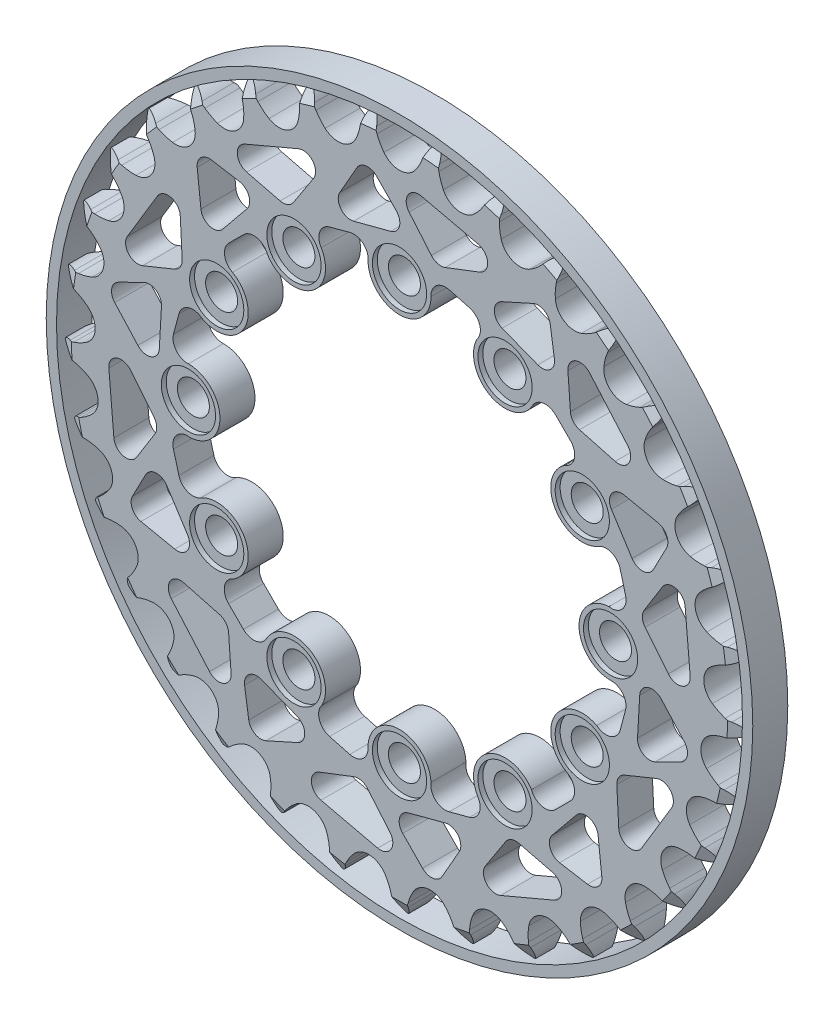
SolidWorks part; units mm, degrees
material "7075-T6 (SN)"
ref_plane "Front Plane" through (0, 0, 0) normal (0, 0, 1) x (1, 0, 0)
ref_plane "Top Plane" through (0, 0, 0) normal (0, 1, 0) x (1, 0, 0)
ref_plane "Right Plane" through (0, 0, 0) normal (1, 0, 0) x (0, 0, -1)
sketch "Work Sketch" plane through (0, 0, 0) normal (0, 0, 1) x (1, 0, 0)
  line L0 (0, 0) -> (0, 160.4542) construction
  line L1 (-112.0919, 66.8027) -> (87.2579, 66.8027) construction
  line L2 (5.0834, 120.8822) -> (5.0834, 112.9699) construction
  line L3 (-12.8497, 70.6081) -> (16.7256, 70.6081) construction
  line L4 (5.0834, 70.6081) -> (-6.0658, 62.2619) construction
  line L5 (5.0834, 70.6081) -> (-4.6352, 66.9715) construction
  line L6 (-4.6352, 66.9715) -> (-6.998, 73.2861)
  line L7 (-11.5114, 65.7464) -> (-7.1525, 65.7464) construction
  line L8 (-11.0622, 124.7602) -> (-11.0622, 110.2345) construction
  line L9 (0, 0) -> (-4.0639, 42.5596) construction
  circle A0 centre (0, 0) radius 66.8027
  circle A1 centre (0, 66.8027) radius 4.0088
  arc A2 (-4.6352, 66.9715) -> (-3.2092, 64.4003) centre (5.0609, 70.6677) ccw
  circle A3 centre (-11.0622, 65.7464) radius 6.4488
  point P23 (-3.2092, 64.4003)
  dimension "D1" = 133.6054
  dimension "D8" = 10.3767
  dimension "D2" = 8.0177
  dimension "D3" = 5.0834
  dimension "D4" = 3.8054
  dimension "D5" = 36.818
  dimension "D6" = 16.303
  dimension "D7" = 10.3767
  dimension "D9" = 1.0563
  dimension "D10" = 11.0622
  dimension "D11" = 5.455
sketch "Teeth Sketch" plane through (0, 0, 0) normal (0, 0, 1) x (1, 0, 0)
  line L0 (5.0224, 68.0064) -> (4.6352, 66.9715)
  line L1 (-8.8439, 92.6176) -> (-5.6513, 59.1829) construction
  line L2 (0, 0) -> (-12.8498, 132.1321) construction
  line L3 (7.9387, 67.7279) -> (8.123, 66.6385)
  line L4 (19011.2087, -199094.3845) -> (-19015.2726, 199136.9441) construction
  line L5 (0, 146.3285) -> (0, 56.9858) construction
  line L6 (17.8019, 65.8269) -> (17.2258, 64.8841)
  line L7 (0, -200000) -> (0, 200160.4542) construction
  line L8 (20.6128, 65.0016) -> (20.5877, 63.897)
  line L9 (-4.6352, 66.9715) -> (-6.998, 73.2861) construction
  line L10 (43.2949, 52.6844) -> (42.861, 51.6682)
  line L11 (-5.0224, 68.0064) -> (-4.6352, 66.9715)
  line L12 (29.938, 61.2683) -> (29.1939, 60.4515)
  line L13 (32.5419, 59.9259) -> (32.3082, 58.846)
  line L14 (40.9921, 54.4953) -> (40.1069, 53.8341)
  line L15 (50.5647, 45.7527) -> (49.5703, 45.271)
  line L16 (52.4831, 43.5387) -> (51.8648, 42.623)
  line L17 (58.3096, 35.3565) -> (57.2421, 35.0716)
  line L18 (59.7744, 32.8194) -> (58.9939, 32.0373)
  line L19 (63.9472, 23.6824) -> (62.845, 23.6047)
  line L20 (64.9053, 20.9139) -> (63.9909, 20.2936)
  line L21 (67.2735, 11.1523) -> (66.1765, 11.2846)
  line L22 (67.6904, 8.2526) -> (66.6751, 7.8165)
  line L23 (68.1683, -1.7808) -> (67.1162, -1.4433)
  line L24 (68.0289, -4.7071) -> (66.9495, -4.9431)
  line L25 (66.5994, -14.6496) -> (65.6302, -14.119)
  line L26 (65.9088, -17.4966) -> (64.8042, -17.524)
  line L27 (62.6234, -26.9889) -> (61.7722, -26.2845)
  line L28 (61.4065, -29.6537) -> (60.3166, -29.4716)
  line L29 (56.3841, -38.3527) -> (55.6815, -37.4999)
  line L30 (54.6848, -40.739) -> (53.6491, -40.354)
  line L31 (48.1068, -48.3304) -> (47.5783, -47.3601)
  line L32 (45.9866, -50.352) -> (45.0425, -49.7779)
  line L33 (38.0909, -56.5613) -> (37.7556, -55.5085)
  line L34 (35.6264, -58.1451) -> (34.808, -57.4027)
  line L35 (26.6983, -62.7479) -> (26.5682, -61.6506)
  line L36 (23.9786, -63.8367) -> (23.3155, -62.9529)
  line L37 (14.3407, -66.6666) -> (14.4207, -65.5646)
  line L38 (11.4641, -67.221) -> (10.9802, -66.2277)
  line L39 (1.4648, -68.1759) -> (1.7519, -67.1089)
  line L40 (-1.4648, -68.1759) -> (-1.7519, -67.1089)
  line L41 (-11.4641, -67.221) -> (-10.9802, -66.2277)
  line L42 (-14.3407, -66.6666) -> (-14.4207, -65.5646)
  line L43 (-23.9786, -63.8367) -> (-23.3155, -62.9529)
  line L44 (-26.6983, -62.7479) -> (-26.5682, -61.6506)
  line L45 (-35.6264, -58.1451) -> (-34.808, -57.4027)
  line L46 (-38.0909, -56.5613) -> (-37.7556, -55.5085)
  line L47 (-45.9866, -50.352) -> (-45.0425, -49.7779)
  line L48 (-48.1068, -48.3304) -> (-47.5783, -47.3601)
  line L49 (-54.6848, -40.739) -> (-53.6491, -40.354)
  line L50 (-56.3841, -38.3527) -> (-55.6815, -37.4999)
  line L51 (-61.4065, -29.6537) -> (-60.3166, -29.4716)
  line L52 (-62.6234, -26.9889) -> (-61.7722, -26.2845)
  line L53 (-65.9088, -17.4966) -> (-64.8042, -17.524)
  line L54 (-66.5994, -14.6496) -> (-65.6302, -14.119)
  line L55 (-68.0289, -4.7071) -> (-66.9495, -4.9431)
  line L56 (-68.1683, -1.7808) -> (-67.1162, -1.4433)
  line L57 (-67.6904, 8.2526) -> (-66.6751, 7.8165)
  line L58 (-67.2735, 11.1523) -> (-66.1765, 11.2846)
  line L59 (-64.9053, 20.9139) -> (-63.9909, 20.2936)
  line L60 (-63.9472, 23.6824) -> (-62.845, 23.6047)
  line L61 (-59.7744, 32.8194) -> (-58.9939, 32.0373)
  line L62 (-58.3096, 35.3565) -> (-57.2421, 35.0716)
  line L63 (-52.4831, 43.5387) -> (-51.8648, 42.623)
  line L64 (-50.5647, 45.7527) -> (-49.5703, 45.271)
  line L65 (-43.2949, 52.6844) -> (-42.861, 51.6682)
  line L66 (-40.9921, 54.4953) -> (-40.1069, 53.8341)
  line L67 (-32.5419, 59.9259) -> (-32.3082, 58.846)
  line L68 (-29.938, 61.2683) -> (-29.1939, 60.4515)
  line L69 (-20.6128, 65.0016) -> (-20.5877, 63.897)
  line L70 (-17.8019, 65.8269) -> (-17.2258, 64.8841)
  line L71 (-7.9387, 67.7279) -> (-8.123, 66.6385)
  arc A0 (-6.7346, 70.5274) -> (-5.0224, 68.0064) centre (-11.0622, 65.7464) cw
  circle A1 centre (-11.0622, 65.7464) radius 6.4488 construction
  arc A2 (-3.2092, 64.4003) -> (-4.6352, 66.9715) centre (5.0609, 70.6677) cw
  arc A3 (-4.6352, 66.9715) -> (-3.2092, 64.4003) centre (5.0609, 70.6677) ccw construction
  circle A4 centre (0, 66.8027) radius 4.0088 construction
  arc A5 (-3.2092, 64.4003) -> (3.2092, 64.4003) centre (0, 66.8027) ccw
  arc A6 (3.2092, 64.4003) -> (4.6352, 66.9715) centre (-5.0609, 70.6677) ccw
  arc A7 (6.7346, 70.5274) -> (5.0224, 68.0064) centre (11.0622, 65.7464) ccw
  arc A8 (6.7346, 70.5274) -> (7.9387, 67.7279) centre (1.5803, 66.6518) cw
  arc A9 (9.0366, 63.8438) -> (8.123, 66.6385) centre (18.3434, 68.4328) cw
  arc A10 (9.0366, 63.8438) -> (15.3391, 62.6291) centre (12.6425, 65.5955) ccw
  arc A11 (15.3391, 62.6291) -> (17.2258, 64.8841) centre (8.4044, 70.3484) ccw
  arc A12 (19.9603, 67.9784) -> (17.8019, 65.8269) centre (23.3049, 62.4647) ccw
  arc A13 (19.9603, 67.9784) -> (20.6128, 65.0016) centre (14.1657, 65.1482) cw
  arc A14 (20.9558, 60.9799) -> (20.5877, 63.897) centre (30.9629, 63.7246) cw
  arc A15 (20.9558, 60.9799) -> (26.9145, 58.5944) centre (24.8281, 62.0175) ccw
  arc A16 (26.9145, 58.5944) -> (29.1939, 60.4515) centre (21.5661, 67.4865) ccw
  arc A17 (32.4645, 62.9724) -> (29.938, 61.2683) centre (34.7052, 56.9254) ccw
  arc A18 (32.4645, 62.9724) -> (32.5419, 59.9259) centre (26.2391, 61.29) cw
  arc A19 (32.1176, 55.912) -> (32.3082, 58.846) centre (42.4634, 56.7133) cw
  arc A20 (32.1176, 55.912) -> (37.5172, 52.4419) centre (36.1163, 56.198) ccw
  arc A21 (37.5172, 52.4419) -> (40.1069, 53.8341) centre (33.9483, 62.1856) ccw
  arc A22 (43.7955, 55.6905) -> (40.9921, 54.4953) centre (44.8513, 49.3287) ccw
  arc A23 (43.7955, 55.6905) -> (43.2949, 52.6844) centre (37.3641, 55.2167) cw
  arc A24 (42.1187, 48.8233) -> (42.861, 51.6682) centre (52.429, 47.6521) cw
  arc A25 (42.1187, 48.8233) -> (46.7639, 44.3941) centre (46.0991, 48.3474) ccw
  arc A26 (46.7639, 44.3941) -> (49.5703, 45.271) centre (45.1035, 54.637) ccw
  arc A27 (53.5435, 46.3957) -> (50.5647, 45.7527) centre (53.3763, 39.9491) ccw
  arc A28 (53.5435, 46.3957) -> (52.4831, 43.5387) centre (47.1387, 47.1476) cw
  arc A29 (50.5974, 39.97) -> (51.8648, 42.623) centre (60.4998, 36.8687) cw
  arc A30 (50.5974, 39.97) -> (54.3205, 34.7417) centre (54.4159, 38.7494) ccw
  arc A31 (54.3205, 34.7417) -> (57.2421, 35.0716) centre (54.6285, 45.1138) ccw
  arc A32 (61.3564, 35.4241) -> (58.3096, 35.3565) centre (59.9721, 29.1257) ccw
  arc A33 (61.3564, 35.4241) -> (59.7744, 32.8194) centre (55.2096, 37.3746) cw
  arc A34 (57.2474, 29.6721) -> (58.9939, 32.0373) centre (66.384, 24.7528) cw
  arc A35 (57.2474, 29.6721) -> (59.9137, 23.8336) centre (60.7659, 27.7508) ccw
  arc A36 (59.9137, 23.8336) -> (62.845, 23.6047) centre (62.1792, 33.96) ccw
  arc A37 (66.9516, 23.1722) -> (63.9472, 23.6824) centre (64.4004, 17.2495) ccw
  arc A38 (66.9516, 23.1722) -> (64.9053, 20.9139) centre (61.2851, 26.2507) cw
  arc A39 (61.8283, 18.3017) -> (63.9909, 20.2936) centre (69.8688, 11.7422) cw
  arc A40 (61.8283, 18.3017) -> (63.3416, 12.0642) centre (64.9196, 15.7493) ccw
  arc A41 (63.3416, 12.0642) -> (66.1765, 11.2846) centre (67.4825, 21.5788) ccw
  arc A42 (70.1271, 10.0828) -> (67.2735, 11.1523) centre (66.5011, 4.7499) ccw
  arc A43 (70.1271, 10.0828) -> (67.6904, 8.2526) centre (65.1456, 14.178) cw
  arc A44 (64.1746, 6.2699) -> (66.6751, 7.8165) centre (70.8284, -1.6927) cw
  arc A45 (64.1746, 6.2699) -> (64.48, -0.1413) centre (66.727, 3.1786) ccw
  arc A46 (64.48, -0.1413) -> (67.1162, -1.4433) centre (70.3468, 8.4177) ccw
  arc A47 (70.768, -3.3711) -> (68.1683, -1.7808) centre (66.1983, -7.9213) ccw
  arc A48 (70.768, -3.3711) -> (68.0289, -4.7071) centre (66.6515, 1.5929) cw
  arc A49 (64.2015, -5.9885) -> (66.9495, -4.9431) centre (69.2281, -15.0665) cw
  arc A50 (64.2015, -5.9885) -> (63.2881, -12.3417) centre (66.1227, -9.507) ccw
  arc A51 (63.2881, -12.3417) -> (65.6302, -14.119) centre (70.6686, -5.0476) ccw
  arc A52 (68.8511, -16.7031) -> (66.5994, -14.6496) centre (63.5029, -20.3063) ccw
  arc A53 (68.8511, -16.7031) -> (65.9088, -17.4966) centre (65.7485, -11.0498) cw
  arc A54 (61.908, -18.0305) -> (64.8042, -17.524) centre (65.1257, -27.8957) cw
  arc A55 (61.908, -18.0305) -> (59.8087, -24.096) centre (63.1286, -21.849) ccw
  arc A56 (59.8087, -24.096) -> (61.7722, -26.2845) centre (68.4363, -18.3305) ccw
  arc A57 (64.4458, -29.4314) -> (62.6234, -26.9889) centre (58.5123, -31.9573) ccw
  arc A58 (64.4458, -29.4314) -> (61.4065, -29.6537) centre (62.4691, -23.2931) cw
  arc A59 (57.3769, -29.4209) -> (60.3166, -29.4716) centre (58.6695, -39.7167) cw
  arc A60 (57.3769, -29.4209) -> (54.1677, -34.9794) centre (57.8528, -33.4013) ccw
  arc A61 (54.1677, -34.9794) -> (55.6815, -37.4999) centre (63.7305, -30.9509) ccw
  arc A62 (57.7113, -41.096) -> (56.3841, -38.3527) centre (51.4069, -42.4533) ccw
  arc A63 (57.7113, -41.096) -> (54.6848, -40.739) centre (56.932, -34.6945) cw
  arc A64 (50.7721, -39.7478) -> (53.6491, -40.354) centre (50.0928, -50.1023) cw
  arc A65 (50.7721, -39.7478) -> (46.5689, -44.5986) centre (50.4861, -43.7465) ccw
  arc A66 (46.5689, -44.5986) -> (47.5783, -47.3601) centre (56.7213, -42.4527) ccw
  arc A67 (48.8909, -51.2753) -> (48.1068, -48.3304) centre (42.4436, -51.415) ccw
  arc A68 (48.8909, -51.2753) -> (45.9866, -50.352) centre (49.3372, -44.842) cw
  arc A69 (42.3322, -48.6382) -> (45.0425, -49.7779) centre (39.7057, -58.677) cw
  arc A70 (42.3322, -48.6382) -> (37.287, -52.6059) centre (41.2947, -52.5105) ccw
  arc A71 (37.287, -52.6059) -> (37.7556, -55.5085) centre (47.662, -52.4201) ccw
  arc A72 (38.3034, -59.6013) -> (38.0909, -56.5613) centre (31.9463, -58.5183) ccw
  arc A73 (38.3034, -59.6013) -> (35.6264, -58.1451) centre (39.9592, -53.3687) cw
  arc A74 (32.3624, -55.7707) -> (34.808, -57.4027) centre (27.8834, -65.131) cw
  arc A75 (32.3624, -55.7707) -> (26.6574, -58.7118) centre (30.6108, -59.3766) ccw
  arc A76 (26.6574, -58.7118) -> (26.5682, -61.6506) centre (36.8801, -60.4929) ccw
  arc A77 (26.3316, -65.7732) -> (26.6983, -62.7479) centre (20.2943, -63.5067) ccw
  arc A78 (26.3316, -65.7732) -> (23.9786, -63.8367) centre (29.137, -59.9666) cw
  arc A79 (21.2229, -60.8875) -> (23.3155, -62.9529) centre (15.0534, -69.2309) cw
  arc A80 (21.2229, -60.8875) -> (15.0644, -62.6958) centre (18.8205, -64.0967) ccw
  arc A81 (15.0644, -62.6958) -> (14.4207, -65.5646) centre (24.7653, -66.3793) ccw
  arc A82 (13.4081, -69.5679) -> (14.3407, -66.6666) centre (7.9088, -66.1998) ccw
  arc A83 (13.4081, -69.5679) -> (11.4641, -67.221) centre (17.2617, -64.3972) cw
  arc A84 (9.3163, -63.8036) -> (10.9802, -66.2277) centre (1.6794, -70.8287) cw
  arc A85 (9.3163, -63.8036) -> (2.9269, -64.4137) centre (6.35, -66.5002) ccw
  arc A86 (2.9269, -64.4137) -> (1.7519, -67.1089) centre (11.7554, -69.8666) ccw
  arc A87 (0, -70.8482) -> (1.4648, -68.1759) centre (-4.7625, -66.5002) ccw
  arc A88 (0, -70.8482) -> (-1.4648, -68.1759) centre (4.7625, -66.5002) cw
  arc A89 (-2.9269, -64.4137) -> (-1.7519, -67.1089) centre (-11.7554, -69.8666) cw
  arc A90 (-2.9269, -64.4137) -> (-9.3163, -63.8036) centre (-6.35, -66.5002) ccw
  arc A91 (-9.3163, -63.8036) -> (-10.9802, -66.2277) centre (-1.6794, -70.8287) ccw
  arc A92 (-13.4081, -69.5679) -> (-11.4641, -67.221) centre (-17.2617, -64.3972) ccw
  arc A93 (-13.4081, -69.5679) -> (-14.3407, -66.6666) centre (-7.9088, -66.1998) cw
  arc A94 (-15.0644, -62.6958) -> (-14.4207, -65.5646) centre (-24.7653, -66.3793) cw
  arc A95 (-15.0644, -62.6958) -> (-21.2229, -60.8875) centre (-18.8205, -64.0967) ccw
  arc A96 (-21.2229, -60.8875) -> (-23.3155, -62.9529) centre (-15.0534, -69.2309) ccw
  arc A97 (-26.3316, -65.7732) -> (-23.9786, -63.8367) centre (-29.137, -59.9666) ccw
  arc A98 (-26.3316, -65.7732) -> (-26.6983, -62.7479) centre (-20.2943, -63.5067) cw
  arc A99 (-26.6574, -58.7118) -> (-26.5682, -61.6506) centre (-36.8801, -60.4929) cw
  arc A100 (-26.6574, -58.7118) -> (-32.3624, -55.7707) centre (-30.6108, -59.3766) ccw
  arc A101 (-32.3624, -55.7707) -> (-34.808, -57.4027) centre (-27.8834, -65.131) ccw
  arc A102 (-38.3034, -59.6013) -> (-35.6264, -58.1451) centre (-39.9592, -53.3687) ccw
  arc A103 (-38.3034, -59.6013) -> (-38.0909, -56.5613) centre (-31.9463, -58.5183) cw
  arc A104 (-37.287, -52.6059) -> (-37.7556, -55.5085) centre (-47.662, -52.4201) cw
  arc A105 (-37.287, -52.6059) -> (-42.3322, -48.6382) centre (-41.2947, -52.5105) ccw
  arc A106 (-42.3322, -48.6382) -> (-45.0425, -49.7779) centre (-39.7057, -58.677) ccw
  arc A107 (-48.8909, -51.2753) -> (-45.9866, -50.352) centre (-49.3372, -44.842) ccw
  arc A108 (-48.8909, -51.2753) -> (-48.1068, -48.3304) centre (-42.4436, -51.415) cw
  arc A109 (-46.5689, -44.5986) -> (-47.5783, -47.3601) centre (-56.7213, -42.4527) cw
  arc A110 (-46.5689, -44.5986) -> (-50.7721, -39.7478) centre (-50.4861, -43.7465) ccw
  arc A111 (-50.7721, -39.7478) -> (-53.6491, -40.354) centre (-50.0928, -50.1023) ccw
  arc A112 (-57.7113, -41.096) -> (-54.6848, -40.739) centre (-56.932, -34.6945) ccw
  arc A113 (-57.7113, -41.096) -> (-56.3841, -38.3527) centre (-51.4069, -42.4533) cw
  arc A114 (-54.1677, -34.9794) -> (-55.6815, -37.4999) centre (-63.7305, -30.9509) cw
  arc A115 (-54.1677, -34.9794) -> (-57.3769, -29.4209) centre (-57.8528, -33.4013) ccw
  arc A116 (-57.3769, -29.4209) -> (-60.3166, -29.4716) centre (-58.6695, -39.7167) ccw
  arc A117 (-64.4458, -29.4314) -> (-61.4065, -29.6537) centre (-62.4691, -23.2931) ccw
  arc A118 (-64.4458, -29.4314) -> (-62.6234, -26.9889) centre (-58.5123, -31.9573) cw
  arc A119 (-59.8087, -24.096) -> (-61.7722, -26.2845) centre (-68.4363, -18.3305) cw
  arc A120 (-59.8087, -24.096) -> (-61.908, -18.0305) centre (-63.1286, -21.849) ccw
  arc A121 (-61.908, -18.0305) -> (-64.8042, -17.524) centre (-65.1257, -27.8957) ccw
  arc A122 (-68.8511, -16.7031) -> (-65.9088, -17.4966) centre (-65.7485, -11.0498) ccw
  arc A123 (-68.8511, -16.7031) -> (-66.5994, -14.6496) centre (-63.5029, -20.3063) cw
  arc A124 (-63.2881, -12.3417) -> (-65.6302, -14.119) centre (-70.6686, -5.0476) cw
  arc A125 (-63.2881, -12.3417) -> (-64.2015, -5.9885) centre (-66.1227, -9.507) ccw
  arc A126 (-64.2015, -5.9885) -> (-66.9495, -4.9431) centre (-69.2281, -15.0665) ccw
  arc A127 (-70.768, -3.3711) -> (-68.0289, -4.7071) centre (-66.6515, 1.5929) ccw
  arc A128 (-70.768, -3.3711) -> (-68.1683, -1.7808) centre (-66.1983, -7.9213) cw
  arc A129 (-64.48, -0.1413) -> (-67.1162, -1.4433) centre (-70.3468, 8.4177) cw
  arc A130 (-64.48, -0.1413) -> (-64.1746, 6.2699) centre (-66.727, 3.1786) ccw
  arc A131 (-64.1746, 6.2699) -> (-66.6751, 7.8165) centre (-70.8284, -1.6927) ccw
  arc A132 (-70.1271, 10.0828) -> (-67.6904, 8.2526) centre (-65.1456, 14.178) ccw
  arc A133 (-70.1271, 10.0828) -> (-67.2735, 11.1523) centre (-66.5011, 4.7499) cw
  arc A134 (-63.3416, 12.0642) -> (-66.1765, 11.2846) centre (-67.4825, 21.5788) cw
  arc A135 (-63.3416, 12.0642) -> (-61.8283, 18.3017) centre (-64.9196, 15.7493) ccw
  arc A136 (-61.8283, 18.3017) -> (-63.9909, 20.2936) centre (-69.8688, 11.7422) ccw
  arc A137 (-66.9516, 23.1722) -> (-64.9053, 20.9139) centre (-61.2851, 26.2507) ccw
  arc A138 (-66.9516, 23.1722) -> (-63.9472, 23.6824) centre (-64.4004, 17.2495) cw
  arc A139 (-59.9137, 23.8336) -> (-62.845, 23.6047) centre (-62.1792, 33.96) cw
  arc A140 (-59.9137, 23.8336) -> (-57.2474, 29.6721) centre (-60.7659, 27.7508) ccw
  arc A141 (-57.2474, 29.6721) -> (-58.9939, 32.0373) centre (-66.384, 24.7528) ccw
  arc A142 (-61.3564, 35.4241) -> (-59.7744, 32.8194) centre (-55.2096, 37.3746) ccw
  arc A143 (-61.3564, 35.4241) -> (-58.3096, 35.3565) centre (-59.9721, 29.1257) cw
  arc A144 (-54.3205, 34.7417) -> (-57.2421, 35.0716) centre (-54.6285, 45.1138) cw
  arc A145 (-54.3205, 34.7417) -> (-50.5974, 39.97) centre (-54.4159, 38.7494) ccw
  arc A146 (-50.5974, 39.97) -> (-51.8648, 42.623) centre (-60.4998, 36.8687) ccw
  arc A147 (-53.5435, 46.3957) -> (-52.4831, 43.5387) centre (-47.1387, 47.1476) ccw
  arc A148 (-53.5435, 46.3957) -> (-50.5647, 45.7527) centre (-53.3763, 39.9491) cw
  arc A149 (-46.7639, 44.3941) -> (-49.5703, 45.271) centre (-45.1035, 54.637) cw
  arc A150 (-46.7639, 44.3941) -> (-42.1187, 48.8233) centre (-46.0991, 48.3474) ccw
  arc A151 (-42.1187, 48.8233) -> (-42.861, 51.6682) centre (-52.429, 47.6521) ccw
  arc A152 (-43.7955, 55.6905) -> (-43.2949, 52.6844) centre (-37.3641, 55.2167) ccw
  arc A153 (-43.7955, 55.6905) -> (-40.9921, 54.4953) centre (-44.8513, 49.3287) cw
  arc A154 (-37.5172, 52.4419) -> (-40.1069, 53.8341) centre (-33.9483, 62.1856) cw
  arc A155 (-37.5172, 52.4419) -> (-32.1176, 55.912) centre (-36.1163, 56.198) ccw
  arc A156 (-32.1176, 55.912) -> (-32.3082, 58.846) centre (-42.4634, 56.7133) ccw
  arc A157 (-32.4645, 62.9724) -> (-32.5419, 59.9259) centre (-26.2391, 61.29) ccw
  arc A158 (-32.4645, 62.9724) -> (-29.938, 61.2683) centre (-34.7052, 56.9254) cw
  arc A159 (-26.9145, 58.5944) -> (-29.1939, 60.4515) centre (-21.5661, 67.4865) cw
  arc A160 (-26.9145, 58.5944) -> (-20.9558, 60.9799) centre (-24.8281, 62.0175) ccw
  arc A161 (-20.9558, 60.9799) -> (-20.5877, 63.897) centre (-30.9629, 63.7246) ccw
  arc A162 (-19.9603, 67.9784) -> (-20.6128, 65.0016) centre (-14.1657, 65.1482) ccw
  arc A163 (-19.9603, 67.9784) -> (-17.8019, 65.8269) centre (-23.3049, 62.4647) cw
  arc A164 (-15.3391, 62.6291) -> (-17.2258, 64.8841) centre (-8.4044, 70.3484) cw
  arc A165 (-15.3391, 62.6291) -> (-9.0366, 63.8438) centre (-12.6425, 65.5955) ccw
  arc A166 (-9.0366, 63.8438) -> (-8.123, 66.6385) centre (-18.3434, 68.4328) ccw
  arc A167 (-6.7346, 70.5274) -> (-7.9387, 67.7279) centre (-1.5803, 66.6518) ccw
  point P77 (0, 0)
  dimension "D1" = 5.455
  dimension "D2" = 5.555
  dimension "D3" = 33
extrude "Extrusion" add sketch "Teeth Sketch" along normal blind 7.2136 contours A0 region at (0, 0, 0)
ref_axis "Axis2" through (0, 0, 38.9715) along (0, 0, -1)
hole_wizard "M6 Clearance Hole1" positions "Sketch6" profile "Sketch7" hole size "M6" standard "ANSI Metric"
sketch "Sketch6" plane through (0, 0, 0) normal (0, 0, -1) x (-1, 0, 0)
  circle A0 centre (0, 0) radius 43.5
  point P0 (0, 43.5)
  dimension "D1" = 87
sketch "Sketch7" plane through (0, 43.5, 0) normal (1, 0, 0) x (0, 1, 0)
  line L0 (0, 0) -> (0, 19.2548)
  line L1 (0, 19.2548) -> (3.3, 17.272)
  line L2 (3.3, 17.272) -> (3.3, 0)
  line L5 (3.3, 0) -> (0, 0)
  line L10 (0, 19.2548) -> (-3.3, 17.272) construction
  line L11 (0, -6.35) -> (0, 107.95) construction
  dimension "Hole Dia." = 6.6
  dimension "Hole Depth" = 17.272
  dimension "Drill Angle" = 118
pattern_circular "CirPattern1" count 12 over 360 about axis through (0, 0, 38.9715) along (0, 0, -1) of "M6 Clearance Hole1"
sketch "Sketch8" plane through (0, 0, 0) normal (0, 0, -1) x (-1, 0, 0)
  circle A0 centre (0, 0) radius 37
  dimension "D1" = 74
extrude "Cut-Extrude1" cut sketch "Sketch8" against normal through all both and the other way through all
ref_plane "Sprocket Center Plane" through (0, 0, 3.6068) normal (0, 0, 1) x (1, 0, 0)
sketch "Pitch Circle" plane through (0, 0, 3.6068) normal (0, 0, -1) x (-1, 0, 0)
  circle A0 centre (0, 0) radius 66.8027 construction
  dimension "D1" = 133.6054
ref_plane "Center Plane" through (0, 0, 3.6068) normal (0, 0, 1) x (1, 0, 0)
ref_axis "Axis1" through (0, 0, 7.2136) along (0, 0, -1)
sketch "Sketch5" plane through (0, 0, 0) normal (1, 0, 0) x (0, 0, -1)
  line L0 (-1.8288, -70.8482) -> (-5.3848, -70.8482)
  line L1 (-7.2136, -51.2753) -> (0, -51.2753) construction
  line L2 (-5.3848, -70.8482) -> (-5.3848, -67.6547)
  line L3 (-5.3848, -67.6547) -> (-7.2136, -67.6547)
  line L4 (-7.2136, -67.6547) -> (-5.3848, -70.8482)
  line L5 (-7.2136, -67.6547) -> (-7.2136, -70.8482)
  line L6 (-7.2136, -70.8482) -> (-5.3848, -70.8482)
  line L8 (-7.2136, -70.8482) -> (0, -70.8482) construction
  dimension "D1" = 3.556
  dimension "D2" = 3.1936
  dimension "D3" = 1.8288
revolve "Cut-Revolve1" cut sketch "Sketch5" angle 360 about axis through (0, 0, 7.2136) along (0, 0, -1) region at (0, -69.7837, 6.604)
mirror "Mirror1" about plane through (0, 0, 3.6068) normal (0, 0, 1) of "Cut-Revolve1"
sketch "Sketch10" plane through (0, 0, 0) normal (0, 0, 1) x (1, 0, 0)
  circle A0 centre (-43.5, 0) radius 5.588
  dimension "D1" = 11.176
extrude "Cut-Extrude2" cut sketch "Sketch10" against normal blind 1.016 from surface starting at face at (-37, 0, 7.2136)
pattern_circular "CirPattern2" count 12 over 360 about axis through (0, 0, 38.9715) along (0, 0, -1) of "Cut-Extrude2"
ref_plane "Half Plane" through (0, 0, 3.6068) normal (0, 0, 1) x (1, 0, 0)
sketch "Motor Shaft Sprocket Dimensions" plane through (0, 0, 3.6068) normal (0, 0, 1) x (1, 0, 0)
  line L0 (0, 0) -> (-177.8, 0)
  line L1 (-177.8, 0) -> (-177.8, 23.6982)
  line L2 (-180.2273, 51.0991) -> (-5.8945, 66.5421)
  line L3 (-187.3193, -2.1104) -> (-23.1174, -62.6753)
  line L4 (-5.8945, 66.5421) -> (0, 0)
  line L5 (0, 0) -> (-23.1174, -62.6753)
  circle A0 centre (-177.8, 23.6982) radius 27.5082
  circle A1 centre (0, 0) radius 66.8027 construction
  dimension "D3" = 55.0164
  dimension "D1" = 177.8
  dimension "D2" = 23.6982
  dimension "D4" = 205.308
sketch "Sketch11" plane through (0, 0, 0) normal (0, 0, 1) x (1, 0, 0)
  line L0 (-167.2094, -55.7997) -> (-36.0913, 46.3337)
  line L1 (-145.9214, -98.8914) -> (14.8674, -56.8186)
  circle A2 centre (-152.1323, -75.1555) radius 24.535
  circle A3 centre (0, 0) radius 58.7316
  dimension "D2" = 117.4631
  dimension "D3" = 49.07
  dimension "D1" = 169.6838
sketch "Sketch12" plane through (0, 0, 7.2136) normal (0, 0, 1) x (1, 0, 0)
  line L0 (0, 43.5) -> (21.75, 37.6721) construction
  line L1 (9.5763, 35.7393) -> (13.8192, 51.5738) construction
  line L2 (10.2476, 46.5861) -> (14.4184, 45.4686) construction
  line L6 (9.4955, 43.681) -> (13.6664, 42.5634) construction
  line L7 (10.2476, 46.5861) -> (14.4184, 45.4686)
  circle A0 centre (21.75, 37.6721) radius 5.588 construction
  circle A1 centre (0, 43.5) radius 5.588 construction
  circle A2 centre (21.75, 37.6721) radius 5.588 construction
  circle A3 centre (0, 43.5) radius 5.588 construction
  circle A4 centre (0, 43.5) radius 6.5 construction
  circle A5 centre (21.75, 37.6721) radius 6.5 construction
  circle A6 centre (0, 0) radius 37 construction
  arc A7 (0, 37) -> (18.5, 32.0429) centre (0, 0) cw
  circle A8 centre (0, 0) radius 37 construction
  arc A9 (10.2476, 46.5861) -> (6.5, 43.5) centre (9.4955, 43.681) ccw
  arc A10 (14.4184, 45.4686) -> (15.9628, 40.6315) centre (13.6664, 42.5634) cw
  arc A20 (0, 37) -> (6.5, 43.5) centre (0, 43.5) ccw
  arc A21 (15.9628, 40.6315) -> (18.5, 32.0429) centre (21.75, 37.6721) ccw
  dimension "D1" = 42.0178
  dimension "D2" = 5.6332
  dimension "D6" = 4.318
  dimension "D7" = 3.0009
extrude "Cut-Extrude3" cut sketch "Sketch12" against normal through all contours A21 A7 A20 A9 L7 A10
pattern_circular "CirPattern3" count 12 over 360 about axis through (0, 0, 7.2136) along (0, 0, -1) of "Cut-Extrude3" reverse direction yes
sketch "Sketch13" plane through (0, 0, 7.2136) normal (0, 0, 1) x (1, 0, 0)
  line L0 (-12.295, 52.6993) -> (-8.767, 58.8746)
  line L1 (-4.7487, 59.3936) -> (-0.6568, 55.2241)
  line L2 (-1.8231, 50.9886) -> (-9.4431, 48.983)
  line L3 (1.9797, 56.3209) -> (6.5673, 50.8863)
  line L4 (9.4175, 50.1531) -> (16.5325, 52.881)
  line L5 (16.1956, 57.7273) -> (4.493, 60.434)
  arc A0 (-4.7487, 59.3936) -> (-8.767, 58.8746) centre (-6.5615, 57.6145) ccw
  arc A1 (-9.4431, 48.983) -> (-12.295, 52.6993) centre (-10.0896, 51.4393) cw
  arc A2 (-1.8231, 50.9886) -> (-0.6568, 55.2241) centre (-2.4696, 53.445) ccw
  arc A3 (9.4175, 50.1531) -> (6.5673, 50.8863) centre (8.5082, 52.5247) cw
  arc A4 (4.493, 60.434) -> (1.9797, 56.3209) centre (3.9206, 57.9593) ccw
  arc A5 (16.5325, 52.881) -> (16.1956, 57.7273) centre (15.6232, 55.2526) ccw
  circle A6 centre (0, 0) radius 43.5 construction
  dimension "D13" = 2.54
  dimension "D15" = 7.62
  dimension "D16" = 2.54
  dimension "D1" = 51.4393
  dimension "D2" = 53.445
  dimension "D3" = 57.6145
  dimension "D4" = 10.0896
  dimension "D5" = 2.4696
  dimension "D6" = 6.5615
  dimension "D7" = 3.9206
  dimension "D8" = 8.5082
  dimension "D9" = 15.6232
  dimension "D10" = 52.5247
  dimension "D11" = 55.2526
  dimension "D12" = 57.9593
  dimension "D14" = 7.112
  dimension "D17" = 7.112
extrude "Cut-Extrude4" cut sketch "Sketch13" against normal through all
pattern_circular "CirPattern5" count 10 over 360 about axis through (0, 0, 38.9715) along (0, 0, -1) of "Cut-Extrude4"
sketch "Sketch14" plane through (0, 0, 7.2136) normal (0, 0, 1) x (1, 0, 0)
  circle A0 centre (0, 0) radius 33.02 construction
  dimension "D1" = 66.04
sketch "Sketch16" plane through (0, 0, 0) normal (0, 0, 1) x (1, 0, 0)
  circle A0 centre (0, 0) radius 70.6924
  circle A1 centre (0, 0) radius 72.8102
extrude "Boss-Extrude1" add sketch "Sketch16" along normal up to surface (7.2136 mm away) separate body up to face at (53.6057, -10.7795, 7.2136)
sketch "Sketch21" plane through (0, 0, 7.2136) normal (0, 0, 1) x (1, 0, 0)
  circle A0 centre (0, 0) radius 19.05 construction
  dimension "D1" = 38.1
sketch "Sketch23" plane through (0, 0, 0) normal (0, 0, -1) x (-1, 0, 0)
  line L12 (-45.4686, 14.4184) -> (-46.5861, 10.2476)
  line L13 (-32.1677, 35.221) -> (-35.221, 32.1677)
  line L14 (-10.2476, 46.5861) -> (-14.4184, 45.4686)
  line L15 (14.4184, 45.4686) -> (10.2476, 46.5861)
  line L16 (35.221, 32.1677) -> (32.1677, 35.221)
  line L17 (46.5861, 10.2476) -> (45.4686, 14.4184)
  line L18 (45.4686, -14.4184) -> (46.5861, -10.2476)
  line L19 (32.1677, -35.221) -> (35.221, -32.1677)
  line L20 (10.2476, -46.5861) -> (14.4184, -45.4686)
  line L21 (-14.4184, -45.4686) -> (-10.2476, -46.5861)
  line L22 (-35.221, -32.1677) -> (-32.1677, -35.221)
  line L23 (-46.5861, -10.2476) -> (-45.4686, -14.4184)
  line L24 (-45.4686, 14.4184) -> (-46.5861, 10.2476)
  line L25 (-32.1677, 35.221) -> (-35.221, 32.1677)
  line L26 (-10.2476, 46.5861) -> (-14.4184, 45.4686)
  line L27 (14.4184, 45.4686) -> (10.2476, 46.5861)
  line L28 (35.221, 32.1677) -> (32.1677, 35.221)
  line L29 (46.5861, 10.2476) -> (45.4686, 14.4184)
  line L30 (45.4686, -14.4184) -> (46.5861, -10.2476)
  line L31 (32.1677, -35.221) -> (35.221, -32.1677)
  line L32 (10.2476, -46.5861) -> (14.4184, -45.4686)
  line L33 (-14.4184, -45.4686) -> (-10.2476, -46.5861)
  line L34 (-35.221, -32.1677) -> (-32.1677, -35.221)
  line L35 (-46.5861, -10.2476) -> (-45.4686, -14.4184)
  arc A39 (-43.5, -6.5) -> (-43.1693, 6.4916) centre (-43.5, 0) ccw
  arc A40 (-46.5861, 10.2476) -> (-43.1693, 6.4916) centre (-43.6941, 9.4463) ccw
  arc A41 (-40.9221, 16.1208) -> (-45.4686, 14.4184) centre (-42.5766, 13.6172) ccw
  arc A42 (-40.9221, 16.1208) -> (-34.14, 27.2065) centre (-37.6721, 21.75) ccw
  arc A43 (-35.221, 32.1677) -> (-34.14, 27.2065) centre (-33.1171, 30.0278) ccw
  arc A44 (-27.3792, 34.4221) -> (-32.1677, 35.221) centre (-30.0638, 33.0811) ccw
  arc A45 (-27.3792, 34.4221) -> (-15.9628, 40.6315) centre (-21.75, 37.6721) ccw
  arc A46 (-14.4184, 45.4686) -> (-15.9628, 40.6315) centre (-13.6664, 42.5634) ccw
  arc A47 (-6.5, 43.5) -> (-10.2476, 46.5861) centre (-9.4955, 43.681) ccw
  arc A48 (-6.5, 43.5) -> (6.4916, 43.1693) centre (0, 43.5) ccw
  arc A49 (10.2476, 46.5861) -> (6.4916, 43.1693) centre (9.4463, 43.6941) ccw
  arc A50 (16.1208, 40.9221) -> (14.4184, 45.4686) centre (13.6172, 42.5766) ccw
  arc A51 (16.1208, 40.9221) -> (27.2065, 34.14) centre (21.75, 37.6721) ccw
  arc A52 (32.1677, 35.221) -> (27.2065, 34.14) centre (30.0278, 33.1171) ccw
  arc A53 (34.4221, 27.3792) -> (35.221, 32.1677) centre (33.0811, 30.0638) ccw
  arc A54 (34.4221, 27.3792) -> (40.6315, 15.9628) centre (37.6721, 21.75) ccw
  arc A55 (45.4686, 14.4184) -> (40.6315, 15.9628) centre (42.5634, 13.6664) ccw
  arc A56 (43.5, 6.5) -> (46.5861, 10.2476) centre (43.681, 9.4955) ccw
  arc A57 (43.5, 6.5) -> (43.1693, -6.4916) centre (43.5, 0) ccw
  arc A58 (46.5861, -10.2476) -> (43.1693, -6.4916) centre (43.6941, -9.4463) ccw
  arc A59 (40.9221, -16.1208) -> (45.4686, -14.4184) centre (42.5766, -13.6172) ccw
  arc A60 (40.9221, -16.1208) -> (34.14, -27.2065) centre (37.6721, -21.75) ccw
  arc A61 (35.221, -32.1677) -> (34.14, -27.2065) centre (33.1171, -30.0278) ccw
  arc A62 (27.3792, -34.4221) -> (32.1677, -35.221) centre (30.0638, -33.0811) ccw
  arc A63 (27.3792, -34.4221) -> (15.9628, -40.6315) centre (21.75, -37.6721) ccw
  arc A64 (14.4184, -45.4686) -> (15.9628, -40.6315) centre (13.6664, -42.5634) ccw
  arc A65 (6.5, -43.5) -> (10.2476, -46.5861) centre (9.4955, -43.681) ccw
  arc A66 (6.5, -43.5) -> (-6.4916, -43.1693) centre (0, -43.5) ccw
  arc A67 (-10.2476, -46.5861) -> (-6.4916, -43.1693) centre (-9.4463, -43.6941) ccw
  arc A68 (-16.1208, -40.9221) -> (-14.4184, -45.4686) centre (-13.6172, -42.5766) ccw
  arc A69 (-16.1208, -40.9221) -> (-27.2065, -34.14) centre (-21.75, -37.6721) ccw
  arc A70 (-32.1677, -35.221) -> (-27.2065, -34.14) centre (-30.0278, -33.1171) ccw
  arc A71 (-34.4221, -27.3792) -> (-35.221, -32.1677) centre (-33.0811, -30.0638) ccw
  arc A72 (-34.4221, -27.3792) -> (-40.6315, -15.9628) centre (-37.6721, -21.75) ccw
  arc A73 (-45.4686, -14.4184) -> (-40.6315, -15.9628) centre (-42.5634, -13.6664) ccw
  arc A74 (-43.5, -6.5) -> (-46.5861, -10.2476) centre (-43.681, -9.4955) ccw
  arc A75 (-43.5, -6.5) -> (-43.1693, 6.4916) centre (-43.5, 0) ccw
  arc A76 (-46.5861, 10.2476) -> (-43.1693, 6.4916) centre (-43.6941, 9.4463) ccw
  arc A77 (-40.9221, 16.1208) -> (-45.4686, 14.4184) centre (-42.5766, 13.6172) ccw
  arc A78 (-40.9221, 16.1208) -> (-34.14, 27.2065) centre (-37.6721, 21.75) ccw
  arc A79 (-35.221, 32.1677) -> (-34.14, 27.2065) centre (-33.1171, 30.0278) ccw
  arc A80 (-27.3792, 34.4221) -> (-32.1677, 35.221) centre (-30.0638, 33.0811) ccw
  arc A81 (-27.3792, 34.4221) -> (-15.9628, 40.6315) centre (-21.75, 37.6721) ccw
  arc A82 (-14.4184, 45.4686) -> (-15.9628, 40.6315) centre (-13.6664, 42.5634) ccw
  arc A83 (-6.5, 43.5) -> (-10.2476, 46.5861) centre (-9.4955, 43.681) ccw
  arc A84 (-6.5, 43.5) -> (6.4916, 43.1693) centre (0, 43.5) ccw
  arc A85 (10.2476, 46.5861) -> (6.4916, 43.1693) centre (9.4463, 43.6941) ccw
  arc A86 (16.1208, 40.9221) -> (14.4184, 45.4686) centre (13.6172, 42.5766) ccw
  arc A87 (16.1208, 40.9221) -> (27.2065, 34.14) centre (21.75, 37.6721) ccw
  arc A88 (32.1677, 35.221) -> (27.2065, 34.14) centre (30.0278, 33.1171) ccw
  arc A89 (34.4221, 27.3792) -> (35.221, 32.1677) centre (33.0811, 30.0638) ccw
  arc A90 (34.4221, 27.3792) -> (40.6315, 15.9628) centre (37.6721, 21.75) ccw
  arc A91 (45.4686, 14.4184) -> (40.6315, 15.9628) centre (42.5634, 13.6664) ccw
  arc A92 (43.5, 6.5) -> (46.5861, 10.2476) centre (43.681, 9.4955) ccw
  arc A93 (43.5, 6.5) -> (43.1693, -6.4916) centre (43.5, 0) ccw
  arc A94 (46.5861, -10.2476) -> (43.1693, -6.4916) centre (43.6941, -9.4463) ccw
  arc A95 (40.9221, -16.1208) -> (45.4686, -14.4184) centre (42.5766, -13.6172) ccw
  arc A96 (40.9221, -16.1208) -> (34.14, -27.2065) centre (37.6721, -21.75) ccw
  arc A97 (35.221, -32.1677) -> (34.14, -27.2065) centre (33.1171, -30.0278) ccw
  arc A98 (27.3792, -34.4221) -> (32.1677, -35.221) centre (30.0638, -33.0811) ccw
  arc A99 (27.3792, -34.4221) -> (15.9628, -40.6315) centre (21.75, -37.6721) ccw
  arc A100 (14.4184, -45.4686) -> (15.9628, -40.6315) centre (13.6664, -42.5634) ccw
  arc A101 (6.5, -43.5) -> (10.2476, -46.5861) centre (9.4955, -43.681) ccw
  arc A102 (6.5, -43.5) -> (-6.4916, -43.1693) centre (0, -43.5) ccw
  arc A103 (-10.2476, -46.5861) -> (-6.4916, -43.1693) centre (-9.4463, -43.6941) ccw
  arc A104 (-16.1208, -40.9221) -> (-14.4184, -45.4686) centre (-13.6172, -42.5766) ccw
  arc A105 (-16.1208, -40.9221) -> (-27.2065, -34.14) centre (-21.75, -37.6721) ccw
  arc A106 (-32.1677, -35.221) -> (-27.2065, -34.14) centre (-30.0278, -33.1171) ccw
  arc A107 (-34.4221, -27.3792) -> (-35.221, -32.1677) centre (-33.0811, -30.0638) ccw
  arc A108 (-34.4221, -27.3792) -> (-40.6315, -15.9628) centre (-37.6721, -21.75) ccw
  arc A109 (-45.4686, -14.4184) -> (-40.6315, -15.9628) centre (-42.5634, -13.6664) ccw
  arc A110 (-43.5, -6.5) -> (-46.5861, -10.2476) centre (-43.681, -9.4955) ccw
  dimension "D1" = 0
sketch "Sketch24" plane through (0, 0, 0) normal (0, 0, -1) x (-1, 0, 0)
  line L24 (-43.0191, 13.7461) -> (-44.1367, 9.5752)
  line L25 (-30.3826, 33.414) -> (-33.4359, 30.3607)
  line L26 (-9.6051, 44.1287) -> (-13.776, 43.0111)
  line L27 (13.7461, 43.0191) -> (9.5752, 44.1367)
  line L28 (33.414, 30.3826) -> (30.3607, 33.4359)
  line L29 (44.1287, 9.6051) -> (43.0111, 13.776)
  line L30 (43.0191, -13.7461) -> (44.1367, -9.5752)
  line L31 (30.3826, -33.414) -> (33.4359, -30.3607)
  line L32 (9.6051, -44.1287) -> (13.776, -43.0111)
  line L33 (-13.7461, -43.0191) -> (-9.5752, -44.1367)
  line L34 (-33.414, -30.3826) -> (-30.3607, -33.4359)
  line L35 (-44.1287, -9.6051) -> (-43.0111, -13.776)
  line L36 (-43.0191, 13.7461) -> (-44.1367, 9.5752)
  line L37 (-30.3826, 33.414) -> (-33.4359, 30.3607)
  line L38 (-9.6051, 44.1287) -> (-13.776, 43.0111)
  line L39 (13.7461, 43.0191) -> (9.5752, 44.1367)
  line L40 (33.414, 30.3826) -> (30.3607, 33.4359)
  line L41 (44.1287, 9.6051) -> (43.0111, 13.776)
  line L42 (43.0191, -13.7461) -> (44.1367, -9.5752)
  line L43 (30.3826, -33.414) -> (33.4359, -30.3607)
  line L44 (9.6051, -44.1287) -> (13.776, -43.0111)
  line L45 (-13.7461, -43.0191) -> (-9.5752, -44.1367)
  line L46 (-33.414, -30.3826) -> (-30.3607, -33.4359)
  line L47 (-44.1287, -9.6051) -> (-43.0111, -13.776)
  arc A72 (-43.6151, -9.0393) -> (-43.4765, 9.04) centre (-43.5, 0) ccw
  arc A73 (-44.1367, 9.5752) -> (-43.4765, 9.04) centre (-43.6941, 9.4463) ccw
  arc A74 (-42.2914, 13.9793) -> (-43.0191, 13.7461) centre (-42.5766, 13.6172) ccw
  arc A75 (-42.2914, 13.9793) -> (-33.1318, 29.5671) centre (-37.6721, 21.75) ccw
  arc A76 (-33.4359, 30.3607) -> (-33.1318, 29.5671) centre (-33.1171, 30.0278) ccw
  arc A77 (-29.6358, 33.2522) -> (-30.3826, 33.414) centre (-30.0638, 33.0811) ccw
  arc A78 (-29.6358, 33.2522) -> (-13.9094, 42.1717) centre (-21.75, 37.6721) ccw
  arc A79 (-13.776, 43.0111) -> (-13.9094, 42.1717) centre (-13.6664, 42.5634) ccw
  arc A80 (-9.0393, 43.6151) -> (-9.6051, 44.1287) centre (-9.4955, 43.681) ccw
  arc A81 (-9.0393, 43.6151) -> (9.04, 43.4765) centre (0, 43.5) ccw
  arc A82 (9.5752, 44.1367) -> (9.04, 43.4765) centre (9.4463, 43.6941) ccw
  arc A83 (13.9793, 42.2914) -> (13.7461, 43.0191) centre (13.6172, 42.5766) ccw
  arc A84 (13.9793, 42.2914) -> (29.5671, 33.1318) centre (21.75, 37.6721) ccw
  arc A85 (30.3607, 33.4359) -> (29.5671, 33.1318) centre (30.0278, 33.1171) ccw
  arc A86 (33.2522, 29.6358) -> (33.414, 30.3826) centre (33.0811, 30.0638) ccw
  arc A87 (33.2522, 29.6358) -> (42.1717, 13.9094) centre (37.6721, 21.75) ccw
  arc A88 (43.0111, 13.776) -> (42.1717, 13.9094) centre (42.5634, 13.6664) ccw
  arc A89 (43.6151, 9.0393) -> (44.1287, 9.6051) centre (43.681, 9.4955) ccw
  arc A90 (43.6151, 9.0393) -> (43.4765, -9.04) centre (43.5, 0) ccw
  arc A91 (44.1367, -9.5752) -> (43.4765, -9.04) centre (43.6941, -9.4463) ccw
  arc A92 (42.2914, -13.9793) -> (43.0191, -13.7461) centre (42.5766, -13.6172) ccw
  arc A93 (42.2914, -13.9793) -> (33.1318, -29.5671) centre (37.6721, -21.75) ccw
  arc A94 (33.4359, -30.3607) -> (33.1318, -29.5671) centre (33.1171, -30.0278) ccw
  arc A95 (29.6358, -33.2522) -> (30.3826, -33.414) centre (30.0638, -33.0811) ccw
  arc A96 (29.6358, -33.2522) -> (13.9094, -42.1717) centre (21.75, -37.6721) ccw
  arc A97 (13.776, -43.0111) -> (13.9094, -42.1717) centre (13.6664, -42.5634) ccw
  arc A98 (9.0393, -43.6151) -> (9.6051, -44.1287) centre (9.4955, -43.681) ccw
  arc A99 (9.0393, -43.6151) -> (-9.04, -43.4765) centre (0, -43.5) ccw
  arc A100 (-9.5752, -44.1367) -> (-9.04, -43.4765) centre (-9.4463, -43.6941) ccw
  arc A101 (-13.9793, -42.2914) -> (-13.7461, -43.0191) centre (-13.6172, -42.5766) ccw
  arc A102 (-13.9793, -42.2914) -> (-29.5671, -33.1318) centre (-21.75, -37.6721) ccw
  arc A103 (-30.3607, -33.4359) -> (-29.5671, -33.1318) centre (-30.0278, -33.1171) ccw
  arc A104 (-33.2522, -29.6358) -> (-33.414, -30.3826) centre (-33.0811, -30.0638) ccw
  arc A105 (-33.2522, -29.6358) -> (-42.1717, -13.9094) centre (-37.6721, -21.75) ccw
  arc A106 (-43.0111, -13.776) -> (-42.1717, -13.9094) centre (-42.5634, -13.6664) ccw
  arc A107 (-43.6151, -9.0393) -> (-44.1287, -9.6051) centre (-43.681, -9.4955) ccw
  arc A108 (-43.6151, -9.0393) -> (-43.4765, 9.04) centre (-43.5, 0) ccw
  arc A109 (-44.1367, 9.5752) -> (-43.4765, 9.04) centre (-43.6941, 9.4463) ccw
  arc A110 (-42.2914, 13.9793) -> (-43.0191, 13.7461) centre (-42.5766, 13.6172) ccw
  arc A111 (-42.2914, 13.9793) -> (-33.1318, 29.5671) centre (-37.6721, 21.75) ccw
  arc A112 (-33.4359, 30.3607) -> (-33.1318, 29.5671) centre (-33.1171, 30.0278) ccw
  arc A113 (-29.6358, 33.2522) -> (-30.3826, 33.414) centre (-30.0638, 33.0811) ccw
  arc A114 (-29.6358, 33.2522) -> (-13.9094, 42.1717) centre (-21.75, 37.6721) ccw
  arc A115 (-13.776, 43.0111) -> (-13.9094, 42.1717) centre (-13.6664, 42.5634) ccw
  arc A116 (-9.0393, 43.6151) -> (-9.6051, 44.1287) centre (-9.4955, 43.681) ccw
  arc A117 (-9.0393, 43.6151) -> (9.04, 43.4765) centre (0, 43.5) ccw
  arc A118 (9.5752, 44.1367) -> (9.04, 43.4765) centre (9.4463, 43.6941) ccw
  arc A119 (13.9793, 42.2914) -> (13.7461, 43.0191) centre (13.6172, 42.5766) ccw
  arc A120 (13.9793, 42.2914) -> (29.5671, 33.1318) centre (21.75, 37.6721) ccw
  arc A121 (30.3607, 33.4359) -> (29.5671, 33.1318) centre (30.0278, 33.1171) ccw
  arc A122 (33.2522, 29.6358) -> (33.414, 30.3826) centre (33.0811, 30.0638) ccw
  arc A123 (33.2522, 29.6358) -> (42.1717, 13.9094) centre (37.6721, 21.75) ccw
  arc A124 (43.0111, 13.776) -> (42.1717, 13.9094) centre (42.5634, 13.6664) ccw
  arc A125 (43.6151, 9.0393) -> (44.1287, 9.6051) centre (43.681, 9.4955) ccw
  arc A126 (43.6151, 9.0393) -> (43.4765, -9.04) centre (43.5, 0) ccw
  arc A127 (44.1367, -9.5752) -> (43.4765, -9.04) centre (43.6941, -9.4463) ccw
  arc A128 (42.2914, -13.9793) -> (43.0191, -13.7461) centre (42.5766, -13.6172) ccw
  arc A129 (42.2914, -13.9793) -> (33.1318, -29.5671) centre (37.6721, -21.75) ccw
  arc A130 (33.4359, -30.3607) -> (33.1318, -29.5671) centre (33.1171, -30.0278) ccw
  arc A131 (29.6358, -33.2522) -> (30.3826, -33.414) centre (30.0638, -33.0811) ccw
  arc A132 (29.6358, -33.2522) -> (13.9094, -42.1717) centre (21.75, -37.6721) ccw
  arc A133 (13.776, -43.0111) -> (13.9094, -42.1717) centre (13.6664, -42.5634) ccw
  arc A134 (9.0393, -43.6151) -> (9.6051, -44.1287) centre (9.4955, -43.681) ccw
  arc A135 (9.0393, -43.6151) -> (-9.04, -43.4765) centre (0, -43.5) ccw
  arc A136 (-9.5752, -44.1367) -> (-9.04, -43.4765) centre (-9.4463, -43.6941) ccw
  arc A137 (-13.9793, -42.2914) -> (-13.7461, -43.0191) centre (-13.6172, -42.5766) ccw
  arc A138 (-13.9793, -42.2914) -> (-29.5671, -33.1318) centre (-21.75, -37.6721) ccw
  arc A139 (-30.3607, -33.4359) -> (-29.5671, -33.1318) centre (-30.0278, -33.1171) ccw
  arc A140 (-33.2522, -29.6358) -> (-33.414, -30.3826) centre (-33.0811, -30.0638) ccw
  arc A141 (-33.2522, -29.6358) -> (-42.1717, -13.9094) centre (-37.6721, -21.75) ccw
  arc A142 (-43.0111, -13.776) -> (-42.1717, -13.9094) centre (-42.5634, -13.6664) ccw
  arc A143 (-43.6151, -9.0393) -> (-44.1287, -9.6051) centre (-43.681, -9.4955) ccw
  dimension "D1" = 2.54
sketch "Sketch25" plane through (0, 0, 0) normal (0, 0, -1) x (-1, 0, 0)
  arc A72 (-37.9692, -10.1738) -> (-37.9692, 10.1738) centre (-43.5, 0) ccw
  arc A73 (-37.9692, 10.1738) -> (-27.7954, 27.7954) centre (-37.6721, 21.75) ccw
  arc A74 (-27.7954, 27.7954) -> (-10.1738, 37.9692) centre (-21.75, 37.6721) ccw
  arc A75 (-10.1738, 37.9692) -> (10.1738, 37.9692) centre (0, 43.5) ccw
  arc A76 (10.1738, 37.9692) -> (27.7954, 27.7954) centre (21.75, 37.6721) ccw
  arc A77 (27.7954, 27.7954) -> (37.9692, 10.1738) centre (37.6721, 21.75) ccw
  arc A78 (37.9692, 10.1738) -> (37.9692, -10.1738) centre (43.5, 0) ccw
  arc A79 (37.9692, -10.1738) -> (27.7954, -27.7954) centre (37.6721, -21.75) ccw
  arc A80 (27.7954, -27.7954) -> (10.1738, -37.9692) centre (21.75, -37.6721) ccw
  arc A81 (10.1738, -37.9692) -> (-10.1738, -37.9692) centre (0, -43.5) ccw
  arc A82 (-10.1738, -37.9692) -> (-27.7954, -27.7954) centre (-21.75, -37.6721) ccw
  arc A83 (-27.7954, -27.7954) -> (-37.9692, -10.1738) centre (-37.6721, -21.75) ccw
  arc A84 (-37.9692, -10.1738) -> (-37.9692, 10.1738) centre (-43.5, 0) ccw
  arc A85 (-37.9692, 10.1738) -> (-27.7954, 27.7954) centre (-37.6721, 21.75) ccw
  arc A86 (-27.7954, 27.7954) -> (-10.1738, 37.9692) centre (-21.75, 37.6721) ccw
  arc A87 (-10.1738, 37.9692) -> (10.1738, 37.9692) centre (0, 43.5) ccw
  arc A88 (10.1738, 37.9692) -> (27.7954, 27.7954) centre (21.75, 37.6721) ccw
  arc A89 (27.7954, 27.7954) -> (37.9692, 10.1738) centre (37.6721, 21.75) ccw
  arc A90 (37.9692, 10.1738) -> (37.9692, -10.1738) centre (43.5, 0) ccw
  arc A91 (37.9692, -10.1738) -> (27.7954, -27.7954) centre (37.6721, -21.75) ccw
  arc A92 (27.7954, -27.7954) -> (10.1738, -37.9692) centre (21.75, -37.6721) ccw
  arc A93 (10.1738, -37.9692) -> (-10.1738, -37.9692) centre (0, -43.5) ccw
  arc A94 (-10.1738, -37.9692) -> (-27.7954, -27.7954) centre (-21.75, -37.6721) ccw
  arc A95 (-27.7954, -27.7954) -> (-37.9692, -10.1738) centre (-37.6721, -21.75) ccw
  dimension "D1" = 2.54
sketch "Sketch39" plane through (0, 0, 7.2136) normal (0, 0, 1) x (1, 0, 0)
  line L2 (-10.6683, 41.4772) -> (-11.5281, 41.2468)
  line L3 (-28.7552, 31.8085) -> (-31.8085, 28.7552)
  line L4 (-29.9776, 30.5861) -> (-30.607, 29.9567)
  line L5 (11.4996, 41.2544) -> (10.6397, 41.4848)
  line L6 (30.5861, 29.9776) -> (29.9567, 30.607)
  line L7 (41.4772, 10.6683) -> (41.2468, 11.5281)
  line L8 (41.2544, -11.4996) -> (41.4848, -10.6397)
  line L9 (29.9776, -30.5861) -> (30.607, -29.9567)
  line L10 (10.6683, -41.4772) -> (11.5281, -41.2468)
  line L11 (-11.4996, -41.2544) -> (-10.6397, -41.4848)
  line L12 (-30.5861, -29.9776) -> (-29.9567, -30.607)
  line L13 (-41.4772, -10.6683) -> (-41.2468, -11.5281)
  line L14 (-41.2544, 11.4996) -> (-41.4848, 10.6397)
  arc A4 (-27.2065, 34.14) -> (-16.1208, 40.9221) centre (-21.75, 37.6721) ccw construction
  arc A5 (-40.6315, 15.9628) -> (-34.4221, 27.3792) centre (-37.6721, 21.75) ccw construction
  arc A6 (-27.2065, 34.14) -> (-16.1208, 40.9221) centre (-21.75, 37.6721) ccw construction
  arc A7 (-40.6315, 15.9628) -> (-34.4221, 27.3792) centre (-37.6721, 21.75) ccw construction
  arc A8 (-31.9621, 18.6443) -> (-31.2163, 27.3445) centre (-41.526, 23.8462) ccw
  arc A9 (-18.3578, 32.1275) -> (-27.3349, 31.1848) centre (-23.8361, 41.0819) cw
  arc A10 (-29.9776, 30.5861) -> (-27.3349, 31.1848) centre (-28.1815, 28.7901) cw
  arc A11 (-30.607, 29.9567) -> (-31.2163, 27.3445) centre (-28.811, 28.1606) ccw
  arc A12 (-18.3578, 32.1275) -> (-13.3619, 39.2891) centre (-24.0395, 41.4144) ccw
  arc A13 (-11.5281, 41.2468) -> (-13.3619, 39.2891) centre (-10.8707, 38.7933) ccw
  arc A14 (-10.6683, 41.4772) -> (-8.0803, 40.6743) centre (-10.0109, 39.0237) cw
  arc A15 (0.1654, 37.0021) -> (-8.0803, 40.6743) centre (-0.1017, 47.496) cw
  arc A16 (0.1654, 37.0021) -> (8.0729, 40.7063) centre (-0.1116, 47.8857) ccw
  arc A17 (10.6397, 41.4848) -> (8.0729, 40.7063) centre (9.9823, 39.0314) ccw
  arc A18 (11.4996, 41.2544) -> (13.3394, 39.2652) centre (10.8422, 38.801) cw
  arc A19 (18.6443, 31.9621) -> (13.3394, 39.2652) centre (23.6599, 41.1836) cw
  arc A20 (18.6443, 31.9621) -> (27.3445, 31.2163) centre (23.8462, 41.526) ccw
  arc A21 (29.9567, 30.607) -> (27.3445, 31.2163) centre (28.1606, 28.811) ccw
  arc A22 (30.5861, 29.9776) -> (31.1848, 27.3349) centre (28.7901, 28.1815) cw
  arc A23 (32.1275, 18.3578) -> (31.1848, 27.3349) centre (41.0819, 23.8361) cw
  arc A24 (32.1275, 18.3578) -> (39.2891, 13.3619) centre (41.4144, 24.0395) ccw
  arc A25 (41.2468, 11.5281) -> (39.2891, 13.3619) centre (38.7933, 10.8707) ccw
  arc A26 (41.4772, 10.6683) -> (40.6743, 8.0803) centre (39.0237, 10.0109) cw
  arc A27 (37.0021, -0.1654) -> (40.6743, 8.0803) centre (47.496, 0.1017) cw
  arc A28 (37.0021, -0.1654) -> (40.7063, -8.0729) centre (47.8857, 0.1116) ccw
  arc A29 (41.4848, -10.6397) -> (40.7063, -8.0729) centre (39.0314, -9.9823) ccw
  arc A30 (41.2544, -11.4996) -> (39.2652, -13.3394) centre (38.801, -10.8422) cw
  arc A31 (31.9621, -18.6443) -> (39.2652, -13.3394) centre (41.1836, -23.6599) cw
  arc A32 (31.9621, -18.6443) -> (31.2163, -27.3445) centre (41.526, -23.8462) ccw
  arc A33 (30.607, -29.9567) -> (31.2163, -27.3445) centre (28.811, -28.1606) ccw
  arc A34 (29.9776, -30.5861) -> (27.3349, -31.1848) centre (28.1815, -28.7901) cw
  arc A35 (18.3578, -32.1275) -> (27.3349, -31.1848) centre (23.8361, -41.0819) cw
  arc A36 (18.3578, -32.1275) -> (13.3619, -39.2891) centre (24.0395, -41.4144) ccw
  arc A37 (11.5281, -41.2468) -> (13.3619, -39.2891) centre (10.8707, -38.7933) ccw
  arc A38 (10.6683, -41.4772) -> (8.0803, -40.6743) centre (10.0109, -39.0237) cw
  arc A39 (-0.1654, -37.0021) -> (8.0803, -40.6743) centre (0.1017, -47.496) cw
  arc A40 (-0.1654, -37.0021) -> (-8.0729, -40.7063) centre (0.1116, -47.8857) ccw
  arc A41 (-10.6397, -41.4848) -> (-8.0729, -40.7063) centre (-9.9823, -39.0314) ccw
  arc A42 (-11.4996, -41.2544) -> (-13.3394, -39.2652) centre (-10.8422, -38.801) cw
  arc A43 (-18.6443, -31.9621) -> (-13.3394, -39.2652) centre (-23.6599, -41.1836) cw
  arc A44 (-18.6443, -31.9621) -> (-27.3445, -31.2163) centre (-23.8462, -41.526) ccw
  arc A45 (-29.9567, -30.607) -> (-27.3445, -31.2163) centre (-28.1606, -28.811) ccw
  arc A46 (-30.5861, -29.9776) -> (-31.1848, -27.3349) centre (-28.7901, -28.1815) cw
  arc A47 (-32.1275, -18.3578) -> (-31.1848, -27.3349) centre (-41.0819, -23.8361) cw
  arc A48 (-32.1275, -18.3578) -> (-39.2891, -13.3619) centre (-41.4144, -24.0395) ccw
  arc A49 (-41.2468, -11.5281) -> (-39.2891, -13.3619) centre (-38.7933, -10.8707) ccw
  arc A50 (-41.4772, -10.6683) -> (-40.6743, -8.0803) centre (-39.0237, -10.0109) cw
  arc A51 (-37.0021, 0.1654) -> (-40.6743, -8.0803) centre (-47.496, -0.1017) cw
  arc A52 (-37.0021, 0.1654) -> (-40.7063, 8.0729) centre (-47.8857, -0.1116) ccw
  arc A53 (-41.4848, 10.6397) -> (-40.7063, 8.0729) centre (-39.0314, 9.9823) ccw
  arc A54 (-41.2544, 11.4996) -> (-39.2652, 13.3394) centre (-38.801, 10.8422) cw
  arc A55 (-31.9621, 18.6443) -> (-39.2652, 13.3394) centre (-41.1836, 23.6599) cw
  point P131 (0, 0)
  dimension "D2" = 2.54
  dimension "D1" = 4.826
  dimension "D3" = 12
sketch "Sketch42" plane through (0, 0, 7.2136) normal (0, 0, 1) x (1, 0, 0)
  line L3 (-13.2533, 44.203) -> (-10.6816, 44.8921)
  line L4 (-34.1434, 31.0901) -> (-31.0901, 34.1434)
  line L5 (-33.5792, 31.6543) -> (-31.6966, 33.5369)
  line L6 (10.6238, 44.9076) -> (13.1955, 44.2185)
  line L7 (31.6543, 33.5792) -> (33.5369, 31.6966)
  line L8 (44.203, 13.2533) -> (44.8921, 10.6816)
  line L9 (44.9076, -10.6238) -> (44.2185, -13.1955)
  line L10 (33.5792, -31.6543) -> (31.6966, -33.5369)
  line L11 (13.2533, -44.203) -> (10.6816, -44.8921)
  line L12 (-10.6238, -44.9076) -> (-13.1955, -44.2185)
  line L13 (-31.6543, -33.5792) -> (-33.5369, -31.6966)
  line L14 (-44.203, -13.2533) -> (-44.8921, -10.6816)
  line L15 (-44.9076, 10.6238) -> (-44.2185, 13.1955)
  arc A0 (-31.9621, 18.6443) -> (-33.5712, 29.4912) centre (-39.9689, 22.9993) ccw
  arc A3 (-40.6315, 15.9628) -> (-34.4221, 27.3792) centre (-37.6721, 21.75) ccw construction
  arc A4 (-33.5792, 31.6543) -> (-33.5712, 29.4912) centre (-32.5015, 30.5767) ccw
  arc A5 (-18.3578, 32.1275) -> (-29.5281, 33.5235) centre (-23.068, 39.8264) cw
  arc A6 (-27.2065, 34.14) -> (-16.1208, 40.9221) centre (-21.75, 37.6721) ccw construction
  arc A7 (-31.6966, 33.5369) -> (-29.5281, 33.5235) centre (-30.619, 32.4592) cw
  arc A8 (-18.3578, 32.1275) -> (-14.328, 42.3257) centre (-23.1145, 39.9024) ccw
  arc A9 (-13.2533, 44.203) -> (-14.328, 42.3257) centre (-12.8588, 42.7309) ccw
  arc A10 (-10.6816, 44.8921) -> (-8.8104, 43.7963) centre (-10.2872, 43.42) cw
  arc A11 (0.1654, 37.0021) -> (-8.8104, 43.7963) centre (-0.0643, 46.0247) cw
  arc A12 (0.1654, 37.0021) -> (8.7545, 43.8191) centre (-0.0665, 46.1137) ccw
  arc A13 (10.6238, 44.9076) -> (8.7545, 43.8191) centre (10.2294, 43.4355) ccw
  arc A14 (13.1955, 44.2185) -> (14.2681, 42.3339) centre (12.801, 42.7464) cw
  arc A15 (18.6443, 31.9621) -> (14.2681, 42.3339) centre (22.9567, 39.8907) cw
  arc A16 (18.6443, 31.9621) -> (29.4912, 33.5712) centre (22.9993, 39.9689) ccw
  arc A17 (31.6543, 33.5792) -> (29.4912, 33.5712) centre (30.5767, 32.5015) ccw
  arc A18 (33.5369, 31.6966) -> (33.5235, 29.5281) centre (32.4592, 30.619) cw
  arc A19 (32.1275, 18.3578) -> (33.5235, 29.5281) centre (39.8264, 23.068) cw
  arc A20 (32.1275, 18.3578) -> (42.3257, 14.328) centre (39.9024, 23.1145) ccw
  arc A21 (44.203, 13.2533) -> (42.3257, 14.328) centre (42.7309, 12.8588) ccw
  arc A22 (44.8921, 10.6816) -> (43.7963, 8.8104) centre (43.42, 10.2872) cw
  arc A23 (37.0021, -0.1654) -> (43.7963, 8.8104) centre (46.0247, 0.0643) cw
  arc A24 (37.0021, -0.1654) -> (43.8191, -8.7545) centre (46.1137, 0.0665) ccw
  arc A25 (44.9076, -10.6238) -> (43.8191, -8.7545) centre (43.4355, -10.2294) ccw
  arc A26 (44.2185, -13.1955) -> (42.3339, -14.2681) centre (42.7464, -12.801) cw
  arc A27 (31.9621, -18.6443) -> (42.3339, -14.2681) centre (39.8907, -22.9567) cw
  arc A28 (31.9621, -18.6443) -> (33.5712, -29.4912) centre (39.9689, -22.9993) ccw
  arc A29 (33.5792, -31.6543) -> (33.5712, -29.4912) centre (32.5015, -30.5767) ccw
  arc A30 (31.6966, -33.5369) -> (29.5281, -33.5235) centre (30.619, -32.4592) cw
  arc A31 (18.3578, -32.1275) -> (29.5281, -33.5235) centre (23.068, -39.8264) cw
  arc A32 (18.3578, -32.1275) -> (14.328, -42.3257) centre (23.1145, -39.9024) ccw
  arc A33 (13.2533, -44.203) -> (14.328, -42.3257) centre (12.8588, -42.7309) ccw
  arc A34 (10.6816, -44.8921) -> (8.8104, -43.7963) centre (10.2872, -43.42) cw
  arc A35 (-0.1654, -37.0021) -> (8.8104, -43.7963) centre (0.0643, -46.0247) cw
  arc A36 (-0.1654, -37.0021) -> (-8.7545, -43.8191) centre (0.0665, -46.1137) ccw
  arc A37 (-10.6238, -44.9076) -> (-8.7545, -43.8191) centre (-10.2294, -43.4355) ccw
  arc A38 (-13.1955, -44.2185) -> (-14.2681, -42.3339) centre (-12.801, -42.7464) cw
  arc A39 (-18.6443, -31.9621) -> (-14.2681, -42.3339) centre (-22.9567, -39.8907) cw
  arc A40 (-18.6443, -31.9621) -> (-29.4912, -33.5712) centre (-22.9993, -39.9689) ccw
  arc A41 (-31.6543, -33.5792) -> (-29.4912, -33.5712) centre (-30.5767, -32.5015) ccw
  arc A42 (-33.5369, -31.6966) -> (-33.5235, -29.5281) centre (-32.4592, -30.619) cw
  arc A43 (-32.1275, -18.3578) -> (-33.5235, -29.5281) centre (-39.8264, -23.068) cw
  arc A44 (-32.1275, -18.3578) -> (-42.3257, -14.328) centre (-39.9024, -23.1145) ccw
  arc A45 (-44.203, -13.2533) -> (-42.3257, -14.328) centre (-42.7309, -12.8588) ccw
  arc A46 (-44.8921, -10.6816) -> (-43.7963, -8.8104) centre (-43.42, -10.2872) cw
  arc A47 (-37.0021, 0.1654) -> (-43.7963, -8.8104) centre (-46.0247, -0.0643) cw
  arc A48 (-37.0021, 0.1654) -> (-43.8191, 8.7545) centre (-46.1137, -0.0665) ccw
  arc A49 (-44.9076, 10.6238) -> (-43.8191, 8.7545) centre (-43.4355, 10.2294) ccw
  arc A50 (-44.2185, 13.1955) -> (-42.3339, 14.2681) centre (-42.7464, 12.801) cw
  arc A51 (-31.9621, 18.6443) -> (-42.3339, 14.2681) centre (-39.8907, 22.9567) cw
  point P133 (0, 0)
  dimension "D2" = 1.524
  dimension "D3" = 1.524
  dimension "D1" = 1.524
  dimension "D4" = 12
ref_plane "Plane1" through (26.3316, -65.7732, 5.3848) normal (0, 0, -1) x (-1, 0, 0)
sketch "Sketch43" plane through (26.3316, -65.7732, 5.3848) normal (0, 0, -1) x (-1, 0, 0)
  circle A1 centre (26.3316, 65.7732) radius 70.981
  dimension "D1" = 141.962
sketch "Sketch44" plane through (0, 0, 0) normal (0, 0, -1) x (-1, 0, 0)
  line L132 (-28.1642, 61.3956) -> (-28.9053, 62.2091)
  line L133 (-22.0094, 64.9698) -> (-21.9844, 63.8696)
  line L134 (-16.0361, 65.6162) -> (-16.6098, 66.5553)
  line L135 (-9.3161, 67.961) -> (-9.4997, 66.876)
  line L136 (-3.3283, 67.4653) -> (-3.714, 68.496)
  line L137 (3.714, 68.496) -> (3.3283, 67.4653)
  line L138 (9.4997, 66.876) -> (9.3161, 67.961)
  line L139 (16.6098, 66.5553) -> (16.0361, 65.6162)
  line L140 (21.9844, 63.8696) -> (22.0094, 64.9698)
  line L141 (28.9053, 62.2091) -> (28.1642, 61.3956)
  line L142 (33.6745, 58.5548) -> (33.9073, 59.6304)
  line L143 (40.1561, 55.6146) -> (39.2744, 54.956)
  line L144 (44.1476, 51.1237) -> (44.5797, 52.1358)
  line L145 (49.9556, 47.0099) -> (48.9652, 46.5301)
  line L146 (53.025, 41.8449) -> (53.6409, 42.7569)
  line L147 (57.9495, 36.7062) -> (56.8862, 36.4225)
  line L148 (59.986, 31.0536) -> (60.7633, 31.8326)
  line L149 (63.849, 25.0759) -> (62.7512, 24.9986)
  line L150 (64.7789, 19.14) -> (65.6896, 19.7578)
  line L151 (67.4408, 12.5392) -> (66.3482, 12.671)
  line L152 (67.2305, 6.5347) -> (68.2417, 6.9689)
  line L153 (68.5951, -0.4506) -> (67.5472, -0.1144)
  line L154 (67.2523, -6.3069) -> (68.3273, -6.0718)
  line L155 (67.2702, -13.4242) -> (66.3049, -12.8958)
  line L156 (64.8433, -18.9205) -> (65.9435, -18.8931)
  line L157 (63.514, -25.9126) -> (62.6662, -25.211)
  line L158 (60.0908, -30.8502) -> (61.1763, -31.0316)
  line L159 (57.4623, -37.4644) -> (56.7625, -36.6151)
  line L160 (53.1664, -41.665) -> (54.198, -42.0485)
  line L161 (49.3337, -47.6622) -> (48.8073, -46.6957)
  line L162 (44.3205, -50.9739) -> (45.2608, -51.5456)
  line L163 (39.422, -56.1373) -> (39.088, -55.0887)
  line L164 (33.8727, -58.4404) -> (34.6878, -59.1798)
  line L165 (28.0856, -62.5835) -> (27.9561, -61.4907)
  line L166 (22.2007, -63.7948) -> (22.8611, -64.6751)
  line L167 (15.734, -66.7678) -> (15.8137, -65.6702)
  line L168 (9.7262, -66.8434) -> (10.2081, -67.8328)
  line L169 (2.8138, -68.5389) -> (3.0997, -67.4762)
  line L170 (-3.0997, -67.4762) -> (-2.8138, -68.5389)
  line L171 (-10.2081, -67.8328) -> (-9.7262, -66.8434)
  line L172 (-15.8137, -65.6702) -> (-15.734, -66.7678)
  line L173 (-22.8611, -64.6751) -> (-22.2007, -63.7948)
  line L174 (-27.9561, -61.4907) -> (-28.0856, -62.5835)
  line L175 (-34.6878, -59.1798) -> (-33.8727, -58.4404)
  line L176 (-39.088, -55.0887) -> (-39.422, -56.1373)
  line L177 (-45.2608, -51.5456) -> (-44.3205, -50.9739)
  line L178 (-48.8073, -46.6957) -> (-49.3337, -47.6622)
  line L179 (-54.198, -42.0485) -> (-53.1664, -41.665)
  line L180 (-56.7625, -36.6151) -> (-57.4623, -37.4644)
  line L181 (-61.1763, -31.0316) -> (-60.0908, -30.8502)
  line L182 (-62.6662, -25.211) -> (-63.514, -25.9126)
  line L183 (-65.9435, -18.8931) -> (-64.8433, -18.9205)
  line L184 (-66.3049, -12.8958) -> (-67.2702, -13.4242)
  line L185 (-68.3273, -6.0718) -> (-67.2523, -6.3069)
  line L186 (-67.5472, -0.1144) -> (-68.5951, -0.4506)
  line L187 (-68.2417, 6.9689) -> (-67.2305, 6.5347)
  line L188 (-66.3482, 12.671) -> (-67.4408, 12.5392)
  line L189 (-65.6896, 19.7578) -> (-64.7789, 19.14)
  line L190 (-62.7512, 24.9986) -> (-63.849, 25.0759)
  line L191 (-60.7633, 31.8326) -> (-59.986, 31.0536)
  line L192 (-56.8862, 36.4225) -> (-57.9495, 36.7062)
  line L193 (-53.6409, 42.7569) -> (-53.025, 41.8449)
  line L194 (-48.9652, 46.5301) -> (-49.9556, 47.0099)
  line L195 (-44.5797, 52.1358) -> (-44.1476, 51.1237)
  line L196 (-39.2744, 54.956) -> (-40.1561, 55.6146)
  line L197 (-33.9073, 59.6304) -> (-33.6745, 58.5548)
  line L198 (-28.1642, 61.3956) -> (-28.9053, 62.2091)
  line L199 (-22.0094, 64.9698) -> (-21.9844, 63.8696)
  line L200 (-16.0361, 65.6162) -> (-16.6098, 66.5553)
  line L201 (-9.3161, 67.961) -> (-9.4997, 66.876)
  line L202 (-3.3283, 67.4653) -> (-3.714, 68.496)
  line L203 (3.714, 68.496) -> (3.3283, 67.4653)
  line L204 (9.4997, 66.876) -> (9.3161, 67.961)
  line L205 (16.6098, 66.5553) -> (16.0361, 65.6162)
  line L206 (21.9844, 63.8696) -> (22.0094, 64.9698)
  line L207 (28.9053, 62.2091) -> (28.1642, 61.3956)
  line L208 (33.6745, 58.5548) -> (33.9073, 59.6304)
  line L209 (40.1561, 55.6146) -> (39.2744, 54.956)
  line L210 (44.1476, 51.1237) -> (44.5797, 52.1358)
  line L211 (49.9556, 47.0099) -> (48.9652, 46.5301)
  line L212 (53.025, 41.8449) -> (53.6409, 42.7569)
  line L213 (57.9495, 36.7062) -> (56.8862, 36.4225)
  line L214 (59.986, 31.0536) -> (60.7633, 31.8326)
  line L215 (63.849, 25.0759) -> (62.7512, 24.9986)
  line L216 (64.7789, 19.14) -> (65.6896, 19.7578)
  line L217 (67.4408, 12.5392) -> (66.3482, 12.671)
  line L218 (67.2305, 6.5347) -> (68.2417, 6.9689)
  line L219 (68.5951, -0.4506) -> (67.5472, -0.1144)
  line L220 (67.2523, -6.3069) -> (68.3273, -6.0718)
  line L221 (67.2702, -13.4242) -> (66.3049, -12.8958)
  line L222 (64.8433, -18.9205) -> (65.9435, -18.8931)
  line L223 (63.514, -25.9126) -> (62.6662, -25.211)
  line L224 (60.0908, -30.8502) -> (61.1763, -31.0316)
  line L225 (57.4623, -37.4644) -> (56.7625, -36.6151)
  line L226 (53.1664, -41.665) -> (54.198, -42.0485)
  line L227 (49.3337, -47.6622) -> (48.8073, -46.6957)
  line L228 (44.3205, -50.9739) -> (45.2608, -51.5456)
  line L229 (39.422, -56.1373) -> (39.088, -55.0887)
  line L230 (33.8727, -58.4404) -> (34.6878, -59.1798)
  line L231 (28.0856, -62.5835) -> (27.9561, -61.4907)
  line L232 (22.2007, -63.7948) -> (22.8611, -64.6751)
  line L233 (15.734, -66.7678) -> (15.8137, -65.6702)
  line L234 (9.7262, -66.8434) -> (10.2081, -67.8328)
  line L235 (2.8138, -68.5389) -> (3.0997, -67.4762)
  line L236 (-3.0997, -67.4762) -> (-2.8138, -68.5389)
  line L237 (-10.2081, -67.8328) -> (-9.7262, -66.8434)
  line L238 (-15.8137, -65.6702) -> (-15.734, -66.7678)
  line L239 (-22.8611, -64.6751) -> (-22.2007, -63.7948)
  line L240 (-27.9561, -61.4907) -> (-28.0856, -62.5835)
  line L241 (-34.6878, -59.1798) -> (-33.8727, -58.4404)
  line L242 (-39.088, -55.0887) -> (-39.422, -56.1373)
  line L243 (-45.2608, -51.5456) -> (-44.3205, -50.9739)
  line L244 (-48.8073, -46.6957) -> (-49.3337, -47.6622)
  line L245 (-54.198, -42.0485) -> (-53.1664, -41.665)
  line L246 (-56.7625, -36.6151) -> (-57.4623, -37.4644)
  line L247 (-61.1763, -31.0316) -> (-60.0908, -30.8502)
  line L248 (-62.6662, -25.211) -> (-63.514, -25.9126)
  line L249 (-65.9435, -18.8931) -> (-64.8433, -18.9205)
  line L250 (-66.3049, -12.8958) -> (-67.2702, -13.4242)
  line L251 (-68.3273, -6.0718) -> (-67.2523, -6.3069)
  line L252 (-67.5472, -0.1144) -> (-68.5951, -0.4506)
  line L253 (-68.2417, 6.9689) -> (-67.2305, 6.5347)
  line L254 (-66.3482, 12.671) -> (-67.4408, 12.5392)
  line L255 (-65.6896, 19.7578) -> (-64.7789, 19.14)
  line L256 (-62.7512, 24.9986) -> (-63.849, 25.0759)
  line L257 (-60.7633, 31.8326) -> (-59.986, 31.0536)
  line L258 (-56.8862, 36.4225) -> (-57.9495, 36.7062)
  line L259 (-53.6409, 42.7569) -> (-53.025, 41.8449)
  line L260 (-48.9652, 46.5301) -> (-49.9556, 47.0099)
  line L261 (-44.5797, 52.1358) -> (-44.1476, 51.1237)
  line L262 (-39.2744, 54.956) -> (-40.1561, 55.6146)
  line L263 (-33.9073, 59.6304) -> (-33.6745, 58.5548)
  arc A330 (-28.9053, 62.2091) -> (-33.3292, 64.6496) centre (-34.7052, 56.9254) ccw
  arc A331 (-28.1642, 61.3956) -> (-26.1907, 59.7893) centre (-21.5661, 67.4865) ccw
  arc A332 (-26.1907, 59.7893) -> (-22.3042, 61.3452) centre (-24.8281, 62.0175) ccw
  arc A333 (-22.3042, 61.3452) -> (-21.9844, 63.8696) centre (-30.9629, 63.7246) ccw
  arc A334 (-20.4919, 69.7889) -> (-22.0094, 64.9698) centre (-14.1657, 65.1482) ccw
  arc A335 (-16.6098, 66.5553) -> (-20.4919, 69.7889) centre (-23.3049, 62.4647) ccw
  arc A336 (-16.0361, 65.6162) -> (-14.4022, 63.6654) centre (-8.4044, 70.3484) ccw
  arc A337 (-14.4022, 63.6654) -> (-10.2915, 64.4577) centre (-12.6425, 65.5955) ccw
  arc A338 (-10.2915, 64.4577) -> (-9.4997, 66.876) centre (-18.3434, 68.4328) ccw
  arc A339 (-6.9139, 72.4058) -> (-9.3161, 67.961) centre (-1.5803, 66.6518) ccw
  arc A340 (-3.714, 68.496) -> (-6.9139, 72.4058) centre (-11.0622, 65.7464) ccw
  arc A341 (-3.3283, 67.4653) -> (-2.0932, 65.2405) centre (5.0609, 70.6677) ccw
  arc A342 (-2.0932, 65.2405) -> (2.0932, 65.2405) centre (0, 66.8027) ccw
  arc A343 (2.0932, 65.2405) -> (3.3283, 67.4653) centre (-5.0609, 70.6677) ccw
  arc A344 (6.9139, 72.4058) -> (3.714, 68.496) centre (11.0622, 65.7464) ccw
  arc A345 (9.3161, 67.961) -> (6.9139, 72.4058) centre (1.5803, 66.6518) ccw
  arc A346 (9.4997, 66.876) -> (10.2915, 64.4577) centre (18.3434, 68.4328) ccw
  arc A347 (10.2915, 64.4577) -> (14.4022, 63.6654) centre (12.6425, 65.5955) ccw
  arc A348 (14.4022, 63.6654) -> (16.0361, 65.6162) centre (8.4044, 70.3484) ccw
  arc A349 (20.4919, 69.7889) -> (16.6098, 66.5553) centre (23.3049, 62.4647) ccw
  arc A350 (22.0094, 64.9698) -> (20.4919, 69.7889) centre (14.1657, 65.1482) ccw
  arc A351 (21.9844, 63.8696) -> (22.3042, 61.3452) centre (30.9629, 63.7246) ccw
  arc A352 (22.3042, 61.3452) -> (26.1907, 59.7893) centre (24.8281, 62.0175) ccw
  arc A353 (26.1907, 59.7893) -> (28.1642, 61.3956) centre (21.5661, 67.4865) ccw
  arc A354 (33.3292, 64.6496) -> (28.9053, 62.2091) centre (34.7052, 56.9254) ccw
  arc A355 (33.9073, 59.6304) -> (33.3292, 64.6496) centre (26.2391, 61.29) ccw
  arc A356 (33.6745, 58.5548) -> (33.5108, 56.0155) centre (42.4634, 56.7133) ccw
  arc A357 (33.5108, 56.0155) -> (37.0326, 53.7522) centre (36.1163, 56.198) ccw
  arc A358 (37.0326, 53.7522) -> (39.2744, 54.956) centre (33.9483, 62.1856) ccw
  arc A359 (44.9619, 57.1737) -> (40.1561, 55.6146) centre (44.8513, 49.3287) ccw
  arc A360 (44.5797, 52.1358) -> (44.9619, 57.1737) centre (37.3641, 55.2167) ccw
  arc A361 (44.1476, 51.1237) -> (43.5062, 48.6613) centre (52.429, 47.6521) ccw
  arc A362 (43.5062, 48.6613) -> (46.536, 45.7724) centre (46.0991, 48.3474) ccw
  arc A363 (46.536, 45.7724) -> (48.9652, 46.5301) centre (45.1035, 54.637) ccw
  arc A364 (54.9696, 47.6314) -> (49.9556, 47.0099) centre (53.3763, 39.9491) ccw
  arc A365 (53.6409, 42.7569) -> (54.9696, 47.6314) centre (47.1387, 47.1476) ccw
  arc A366 (53.025, 41.8449) -> (51.9292, 39.5483) centre (60.4998, 36.8687) ccw
  arc A367 (51.9292, 39.5483) -> (54.3575, 36.1382) centre (54.4159, 38.7494) ccw
  arc A368 (54.3575, 36.1382) -> (56.8862, 36.4225) centre (54.6285, 45.1138) ccw
  arc A369 (62.9905, 36.3676) -> (57.9495, 36.7062) centre (59.9721, 29.1257) ccw
  arc A370 (60.7633, 31.8326) -> (62.9905, 36.3676) centre (55.2096, 37.3746) ccw
  arc A371 (59.986, 31.0536) -> (58.4754, 29.0059) centre (66.384, 24.7528) ccw
  arc A372 (58.4754, 29.0059) -> (60.2144, 25.1979) centre (60.7659, 27.7508) ccw
  arc A373 (60.2144, 25.1979) -> (62.7512, 24.9986) centre (62.1792, 33.96) ccw
  arc A374 (68.7348, 23.7893) -> (63.849, 25.0759) centre (64.4004, 17.2495) ccw
  arc A375 (65.6896, 19.7578) -> (68.7348, 23.7893) centre (61.2851, 26.2507) ccw
  arc A376 (64.7789, 19.14) -> (62.908, 17.4152) centre (69.8688, 11.7422) ccw
  arc A377 (62.908, 17.4152) -> (63.895, 13.3469) centre (64.9196, 15.7493) ccw
  arc A378 (63.895, 13.3469) -> (66.3482, 12.671) centre (67.4825, 21.5788) ccw
  arc A379 (71.9948, 10.3513) -> (67.4408, 12.5392) centre (66.5011, 4.7499) ccw
  arc A380 (68.2417, 6.9689) -> (71.9948, 10.3513) centre (65.1456, 14.178) ccw
  arc A381 (67.2305, 6.5347) -> (65.0671, 5.1951) centre (70.8284, -1.6927) ccw
  arc A382 (65.0671, 5.1951) -> (65.2662, 1.0135) centre (66.727, 3.1786) ccw
  arc A383 (65.2662, 1.0135) -> (67.5472, -0.1144) centre (70.3468, 8.4177) ccw
  arc A384 (72.6528, -3.4609) -> (68.5951, -0.4506) centre (66.1983, -7.9213) ccw
  arc A385 (68.3273, -6.0718) -> (72.6528, -3.4609) centre (66.6515, 1.5929) ccw
  arc A386 (67.2523, -6.3069) -> (64.8744, -7.2128) centre (69.2281, -15.0665) ccw
  arc A387 (64.8744, -7.2128) -> (64.2786, -11.3566) centre (66.1227, -9.507) ccw
  arc A388 (64.2786, -11.3566) -> (66.3049, -12.8958) centre (70.6686, -5.0476) ccw
  arc A389 (70.6849, -17.148) -> (67.2702, -13.4242) centre (63.5029, -20.3063) ccw
  arc A390 (65.9435, -18.8931) -> (70.6849, -17.148) centre (65.7485, -11.0498) ccw
  arc A391 (64.8433, -18.9205) -> (62.337, -19.36) centre (65.1257, -27.8957) ccw
  arc A392 (62.337, -19.36) -> (60.9678, -23.3161) centre (63.1286, -21.849) ccw
  arc A393 (60.9678, -23.3161) -> (62.6662, -25.211) centre (68.4363, -18.3305) ccw
  arc A394 (66.1622, -30.2153) -> (63.514, -25.9126) centre (58.5123, -31.9573) ccw
  arc A395 (61.1763, -31.0316) -> (66.1622, -30.2153) centre (62.4691, -23.2931) ccw
  arc A396 (60.0908, -30.8502) -> (57.5466, -30.8075) centre (58.6695, -39.7167) ccw
  arc A397 (57.5466, -30.8075) -> (55.4534, -34.433) centre (57.8528, -33.4013) ccw
  arc A398 (55.4534, -34.433) -> (56.7625, -36.6151) centre (63.7305, -30.9509) ccw
  arc A399 (59.2483, -42.1905) -> (57.4623, -37.4644) centre (51.4069, -42.4533) ccw
  arc A400 (54.198, -42.0485) -> (59.2483, -42.1905) centre (56.932, -34.6945) ccw
  arc A401 (53.1664, -41.665) -> (50.6762, -41.1416) centre (50.0928, -50.1023) ccw
  arc A402 (50.6762, -41.1416) -> (47.9348, -44.3054) centre (50.4861, -43.7465) ccw
  arc A403 (47.9348, -44.3054) -> (48.8073, -46.6957) centre (56.7213, -42.4527) ccw
  arc A404 (50.193, -52.6409) -> (49.3337, -47.6622) centre (42.4436, -51.415) ccw
  arc A405 (45.2608, -51.5456) -> (50.193, -52.6409) centre (49.3372, -44.842) ccw
  arc A406 (44.3205, -50.9739) -> (41.9744, -49.9886) centre (39.7057, -58.677) ccw
  arc A407 (41.9744, -49.9886) -> (38.6837, -52.5764) centre (41.2947, -52.5105) ccw
  arc A408 (38.6837, -52.5764) -> (39.088, -55.0887) centre (47.662, -52.4201) ccw
  arc A409 (39.3236, -61.1887) -> (39.422, -56.1373) centre (31.9463, -58.5183) ccw
  arc A410 (34.6878, -59.1798) -> (39.3236, -61.1887) centre (39.9592, -53.3687) ccw
  arc A411 (33.8727, -58.4404) -> (31.7554, -57.029) centre (27.8834, -65.131) ccw
  arc A412 (31.7554, -57.029) -> (28.0345, -58.9473) centre (30.6108, -59.3766) ccw
  arc A413 (28.0345, -58.9473) -> (27.9561, -61.4907) centre (36.8801, -60.4929) ccw
  arc A414 (27.0329, -67.525) -> (28.0856, -62.5835) centre (20.2943, -63.5067) ccw
  arc A415 (22.8611, -64.6751) -> (27.0329, -67.525) centre (29.137, -59.9666) ccw
  arc A416 (22.2007, -63.7948) -> (20.3888, -62.0081) centre (15.0534, -69.2309) ccw
  arc A417 (20.3888, -62.0081) -> (16.372, -63.1876) centre (18.8205, -64.0967) ccw
  arc A418 (16.372, -63.1876) -> (15.8137, -65.6702) centre (24.7653, -66.3793) ccw
  arc A419 (13.7652, -71.4208) -> (15.734, -66.7678) centre (7.9088, -66.1998) ccw
  arc A420 (10.2081, -67.8328) -> (13.7652, -71.4208) centre (17.2617, -64.3972) ccw
  arc A421 (9.7262, -66.8434) -> (8.2852, -64.7462) centre (1.6794, -70.8287) ccw
  arc A422 (8.2852, -64.7462) -> (4.1178, -65.1441) centre (6.35, -66.5002) ccw
  arc A423 (4.1178, -65.1441) -> (3.0997, -67.4762) centre (11.7554, -69.8666) ccw
  arc A424 (0, -72.7352) -> (2.8138, -68.5389) centre (-4.7625, -66.5002) ccw
  arc A425 (-2.8138, -68.5389) -> (0, -72.7352) centre (4.7625, -66.5002) ccw
  arc A426 (-3.0997, -67.4762) -> (-4.1178, -65.1441) centre (-11.7554, -69.8666) ccw
  arc A427 (-4.1178, -65.1441) -> (-8.2852, -64.7462) centre (-6.35, -66.5002) ccw
  arc A428 (-8.2852, -64.7462) -> (-9.7262, -66.8434) centre (-1.6794, -70.8287) ccw
  arc A429 (-13.7652, -71.4208) -> (-10.2081, -67.8328) centre (-17.2617, -64.3972) ccw
  arc A430 (-15.734, -66.7678) -> (-13.7652, -71.4208) centre (-7.9088, -66.1998) ccw
  arc A431 (-15.8137, -65.6702) -> (-16.372, -63.1876) centre (-24.7653, -66.3793) ccw
  arc A432 (-16.372, -63.1876) -> (-20.3888, -62.0081) centre (-18.8205, -64.0967) ccw
  arc A433 (-20.3888, -62.0081) -> (-22.2007, -63.7948) centre (-15.0534, -69.2309) ccw
  arc A434 (-27.0329, -67.525) -> (-22.8611, -64.6751) centre (-29.137, -59.9666) ccw
  arc A435 (-28.0856, -62.5835) -> (-27.0329, -67.525) centre (-20.2943, -63.5067) ccw
  arc A436 (-27.9561, -61.4907) -> (-28.0345, -58.9473) centre (-36.8801, -60.4929) ccw
  arc A437 (-28.0345, -58.9473) -> (-31.7554, -57.029) centre (-30.6108, -59.3766) ccw
  arc A438 (-31.7554, -57.029) -> (-33.8727, -58.4404) centre (-27.8834, -65.131) ccw
  arc A439 (-39.3236, -61.1887) -> (-34.6878, -59.1798) centre (-39.9592, -53.3687) ccw
  arc A440 (-39.422, -56.1373) -> (-39.3236, -61.1887) centre (-31.9463, -58.5183) ccw
  arc A441 (-39.088, -55.0887) -> (-38.6837, -52.5764) centre (-47.662, -52.4201) ccw
  arc A442 (-38.6837, -52.5764) -> (-41.9744, -49.9886) centre (-41.2947, -52.5105) ccw
  arc A443 (-41.9744, -49.9886) -> (-44.3205, -50.9739) centre (-39.7057, -58.677) ccw
  arc A444 (-50.193, -52.6409) -> (-45.2608, -51.5456) centre (-49.3372, -44.842) ccw
  arc A445 (-49.3337, -47.6622) -> (-50.193, -52.6409) centre (-42.4436, -51.415) ccw
  arc A446 (-48.8073, -46.6957) -> (-47.9348, -44.3054) centre (-56.7213, -42.4527) ccw
  arc A447 (-47.9348, -44.3054) -> (-50.6762, -41.1416) centre (-50.4861, -43.7465) ccw
  arc A448 (-50.6762, -41.1416) -> (-53.1664, -41.665) centre (-50.0928, -50.1023) ccw
  arc A449 (-59.2483, -42.1905) -> (-54.198, -42.0485) centre (-56.932, -34.6945) ccw
  arc A450 (-57.4623, -37.4644) -> (-59.2483, -42.1905) centre (-51.4069, -42.4533) ccw
  arc A451 (-56.7625, -36.6151) -> (-55.4534, -34.433) centre (-63.7305, -30.9509) ccw
  arc A452 (-55.4534, -34.433) -> (-57.5466, -30.8075) centre (-57.8528, -33.4013) ccw
  arc A453 (-57.5466, -30.8075) -> (-60.0908, -30.8502) centre (-58.6695, -39.7167) ccw
  arc A454 (-66.1622, -30.2153) -> (-61.1763, -31.0316) centre (-62.4691, -23.2931) ccw
  arc A455 (-63.514, -25.9126) -> (-66.1622, -30.2153) centre (-58.5123, -31.9573) ccw
  arc A456 (-62.6662, -25.211) -> (-60.9678, -23.3161) centre (-68.4363, -18.3305) ccw
  arc A457 (-60.9678, -23.3161) -> (-62.337, -19.36) centre (-63.1286, -21.849) ccw
  arc A458 (-62.337, -19.36) -> (-64.8433, -18.9205) centre (-65.1257, -27.8957) ccw
  arc A459 (-70.6849, -17.148) -> (-65.9435, -18.8931) centre (-65.7485, -11.0498) ccw
  arc A460 (-67.2702, -13.4242) -> (-70.6849, -17.148) centre (-63.5029, -20.3063) ccw
  arc A461 (-66.3049, -12.8958) -> (-64.2786, -11.3566) centre (-70.6686, -5.0476) ccw
  arc A462 (-64.2786, -11.3566) -> (-64.8744, -7.2128) centre (-66.1227, -9.507) ccw
  arc A463 (-64.8744, -7.2128) -> (-67.2523, -6.3069) centre (-69.2281, -15.0665) ccw
  arc A464 (-72.6528, -3.4609) -> (-68.3273, -6.0718) centre (-66.6515, 1.5929) ccw
  arc A465 (-68.5951, -0.4506) -> (-72.6528, -3.4609) centre (-66.1983, -7.9213) ccw
  arc A466 (-67.5472, -0.1144) -> (-65.2662, 1.0135) centre (-70.3468, 8.4177) ccw
  arc A467 (-65.2662, 1.0135) -> (-65.0671, 5.1951) centre (-66.727, 3.1786) ccw
  arc A468 (-65.0671, 5.1951) -> (-67.2305, 6.5347) centre (-70.8284, -1.6927) ccw
  arc A469 (-71.9948, 10.3513) -> (-68.2417, 6.9689) centre (-65.1456, 14.178) ccw
  arc A470 (-67.4408, 12.5392) -> (-71.9948, 10.3513) centre (-66.5011, 4.7499) ccw
  arc A471 (-66.3482, 12.671) -> (-63.895, 13.3469) centre (-67.4825, 21.5788) ccw
  arc A472 (-63.895, 13.3469) -> (-62.908, 17.4152) centre (-64.9196, 15.7493) ccw
  arc A473 (-62.908, 17.4152) -> (-64.7789, 19.14) centre (-69.8688, 11.7422) ccw
  arc A474 (-68.7348, 23.7893) -> (-65.6896, 19.7578) centre (-61.2851, 26.2507) ccw
  arc A475 (-63.849, 25.0759) -> (-68.7348, 23.7893) centre (-64.4004, 17.2495) ccw
  arc A476 (-62.7512, 24.9986) -> (-60.2144, 25.1979) centre (-62.1792, 33.96) ccw
  arc A477 (-60.2144, 25.1979) -> (-58.4754, 29.0059) centre (-60.7659, 27.7508) ccw
  arc A478 (-58.4754, 29.0059) -> (-59.986, 31.0536) centre (-66.384, 24.7528) ccw
  arc A479 (-62.9905, 36.3676) -> (-60.7633, 31.8326) centre (-55.2096, 37.3746) ccw
  arc A480 (-57.9495, 36.7062) -> (-62.9905, 36.3676) centre (-59.9721, 29.1257) ccw
  arc A481 (-56.8862, 36.4225) -> (-54.3575, 36.1382) centre (-54.6285, 45.1138) ccw
  arc A482 (-54.3575, 36.1382) -> (-51.9292, 39.5483) centre (-54.4159, 38.7494) ccw
  arc A483 (-51.9292, 39.5483) -> (-53.025, 41.8449) centre (-60.4998, 36.8687) ccw
  arc A484 (-54.9696, 47.6314) -> (-53.6409, 42.7569) centre (-47.1387, 47.1476) ccw
  arc A485 (-49.9556, 47.0099) -> (-54.9696, 47.6314) centre (-53.3763, 39.9491) ccw
  arc A486 (-48.9652, 46.5301) -> (-46.536, 45.7724) centre (-45.1035, 54.637) ccw
  arc A487 (-46.536, 45.7724) -> (-43.5062, 48.6613) centre (-46.0991, 48.3474) ccw
  arc A488 (-43.5062, 48.6613) -> (-44.1476, 51.1237) centre (-52.429, 47.6521) ccw
  arc A489 (-44.9619, 57.1737) -> (-44.5797, 52.1358) centre (-37.3641, 55.2167) ccw
  arc A490 (-40.1561, 55.6146) -> (-44.9619, 57.1737) centre (-44.8513, 49.3287) ccw
  arc A491 (-39.2744, 54.956) -> (-37.0326, 53.7522) centre (-33.9483, 62.1856) ccw
  arc A492 (-37.0326, 53.7522) -> (-33.5108, 56.0155) centre (-36.1163, 56.198) ccw
  arc A493 (-33.5108, 56.0155) -> (-33.6745, 58.5548) centre (-42.4634, 56.7133) ccw
  arc A494 (-33.3292, 64.6496) -> (-33.9073, 59.6304) centre (-26.2391, 61.29) ccw
  arc A495 (-28.9053, 62.2091) -> (-33.3292, 64.6496) centre (-34.7052, 56.9254) ccw
  arc A496 (-28.1642, 61.3956) -> (-26.1907, 59.7893) centre (-21.5661, 67.4865) ccw
  arc A497 (-26.1907, 59.7893) -> (-22.3042, 61.3452) centre (-24.8281, 62.0175) ccw
  arc A498 (-22.3042, 61.3452) -> (-21.9844, 63.8696) centre (-30.9629, 63.7246) ccw
  arc A499 (-20.4919, 69.7889) -> (-22.0094, 64.9698) centre (-14.1657, 65.1482) ccw
  arc A500 (-16.6098, 66.5553) -> (-20.4919, 69.7889) centre (-23.3049, 62.4647) ccw
  arc A501 (-16.0361, 65.6162) -> (-14.4022, 63.6654) centre (-8.4044, 70.3484) ccw
  arc A502 (-14.4022, 63.6654) -> (-10.2915, 64.4577) centre (-12.6425, 65.5955) ccw
  arc A503 (-10.2915, 64.4577) -> (-9.4997, 66.876) centre (-18.3434, 68.4328) ccw
  arc A504 (-6.9139, 72.4058) -> (-9.3161, 67.961) centre (-1.5803, 66.6518) ccw
  arc A505 (-3.714, 68.496) -> (-6.9139, 72.4058) centre (-11.0622, 65.7464) ccw
  arc A506 (-3.3283, 67.4653) -> (-2.0932, 65.2405) centre (5.0609, 70.6677) ccw
  arc A507 (-2.0932, 65.2405) -> (2.0932, 65.2405) centre (0, 66.8027) ccw
  arc A508 (2.0932, 65.2405) -> (3.3283, 67.4653) centre (-5.0609, 70.6677) ccw
  arc A509 (6.9139, 72.4058) -> (3.714, 68.496) centre (11.0622, 65.7464) ccw
  arc A510 (9.3161, 67.961) -> (6.9139, 72.4058) centre (1.5803, 66.6518) ccw
  arc A511 (9.4997, 66.876) -> (10.2915, 64.4577) centre (18.3434, 68.4328) ccw
  arc A512 (10.2915, 64.4577) -> (14.4022, 63.6654) centre (12.6425, 65.5955) ccw
  arc A513 (14.4022, 63.6654) -> (16.0361, 65.6162) centre (8.4044, 70.3484) ccw
  arc A514 (20.4919, 69.7889) -> (16.6098, 66.5553) centre (23.3049, 62.4647) ccw
  arc A515 (22.0094, 64.9698) -> (20.4919, 69.7889) centre (14.1657, 65.1482) ccw
  arc A516 (21.9844, 63.8696) -> (22.3042, 61.3452) centre (30.9629, 63.7246) ccw
  arc A517 (22.3042, 61.3452) -> (26.1907, 59.7893) centre (24.8281, 62.0175) ccw
  arc A518 (26.1907, 59.7893) -> (28.1642, 61.3956) centre (21.5661, 67.4865) ccw
  arc A519 (33.3292, 64.6496) -> (28.9053, 62.2091) centre (34.7052, 56.9254) ccw
  arc A520 (33.9073, 59.6304) -> (33.3292, 64.6496) centre (26.2391, 61.29) ccw
  arc A521 (33.6745, 58.5548) -> (33.5108, 56.0155) centre (42.4634, 56.7133) ccw
  arc A522 (33.5108, 56.0155) -> (37.0326, 53.7522) centre (36.1163, 56.198) ccw
  arc A523 (37.0326, 53.7522) -> (39.2744, 54.956) centre (33.9483, 62.1856) ccw
  arc A524 (44.9619, 57.1737) -> (40.1561, 55.6146) centre (44.8513, 49.3287) ccw
  arc A525 (44.5797, 52.1358) -> (44.9619, 57.1737) centre (37.3641, 55.2167) ccw
  arc A526 (44.1476, 51.1237) -> (43.5062, 48.6613) centre (52.429, 47.6521) ccw
  arc A527 (43.5062, 48.6613) -> (46.536, 45.7724) centre (46.0991, 48.3474) ccw
  arc A528 (46.536, 45.7724) -> (48.9652, 46.5301) centre (45.1035, 54.637) ccw
  arc A529 (54.9696, 47.6314) -> (49.9556, 47.0099) centre (53.3763, 39.9491) ccw
  arc A530 (53.6409, 42.7569) -> (54.9696, 47.6314) centre (47.1387, 47.1476) ccw
  arc A531 (53.025, 41.8449) -> (51.9292, 39.5483) centre (60.4998, 36.8687) ccw
  arc A532 (51.9292, 39.5483) -> (54.3575, 36.1382) centre (54.4159, 38.7494) ccw
  arc A533 (54.3575, 36.1382) -> (56.8862, 36.4225) centre (54.6285, 45.1138) ccw
  arc A534 (62.9905, 36.3676) -> (57.9495, 36.7062) centre (59.9721, 29.1257) ccw
  arc A535 (60.7633, 31.8326) -> (62.9905, 36.3676) centre (55.2096, 37.3746) ccw
  arc A536 (59.986, 31.0536) -> (58.4754, 29.0059) centre (66.384, 24.7528) ccw
  arc A537 (58.4754, 29.0059) -> (60.2144, 25.1979) centre (60.7659, 27.7508) ccw
  arc A538 (60.2144, 25.1979) -> (62.7512, 24.9986) centre (62.1792, 33.96) ccw
  arc A539 (68.7348, 23.7893) -> (63.849, 25.0759) centre (64.4004, 17.2495) ccw
  arc A540 (65.6896, 19.7578) -> (68.7348, 23.7893) centre (61.2851, 26.2507) ccw
  arc A541 (64.7789, 19.14) -> (62.908, 17.4152) centre (69.8688, 11.7422) ccw
  arc A542 (62.908, 17.4152) -> (63.895, 13.3469) centre (64.9196, 15.7493) ccw
  arc A543 (63.895, 13.3469) -> (66.3482, 12.671) centre (67.4825, 21.5788) ccw
  arc A544 (71.9948, 10.3513) -> (67.4408, 12.5392) centre (66.5011, 4.7499) ccw
  arc A545 (68.2417, 6.9689) -> (71.9948, 10.3513) centre (65.1456, 14.178) ccw
  arc A546 (67.2305, 6.5347) -> (65.0671, 5.1951) centre (70.8284, -1.6927) ccw
  arc A547 (65.0671, 5.1951) -> (65.2662, 1.0135) centre (66.727, 3.1786) ccw
  arc A548 (65.2662, 1.0135) -> (67.5472, -0.1144) centre (70.3468, 8.4177) ccw
  arc A549 (72.6528, -3.4609) -> (68.5951, -0.4506) centre (66.1983, -7.9213) ccw
  arc A550 (68.3273, -6.0718) -> (72.6528, -3.4609) centre (66.6515, 1.5929) ccw
  arc A551 (67.2523, -6.3069) -> (64.8744, -7.2128) centre (69.2281, -15.0665) ccw
  arc A552 (64.8744, -7.2128) -> (64.2786, -11.3566) centre (66.1227, -9.507) ccw
  arc A553 (64.2786, -11.3566) -> (66.3049, -12.8958) centre (70.6686, -5.0476) ccw
  arc A554 (70.6849, -17.148) -> (67.2702, -13.4242) centre (63.5029, -20.3063) ccw
  arc A555 (65.9435, -18.8931) -> (70.6849, -17.148) centre (65.7485, -11.0498) ccw
  arc A556 (64.8433, -18.9205) -> (62.337, -19.36) centre (65.1257, -27.8957) ccw
  arc A557 (62.337, -19.36) -> (60.9678, -23.3161) centre (63.1286, -21.849) ccw
  arc A558 (60.9678, -23.3161) -> (62.6662, -25.211) centre (68.4363, -18.3305) ccw
  arc A559 (66.1622, -30.2153) -> (63.514, -25.9126) centre (58.5123, -31.9573) ccw
  arc A560 (61.1763, -31.0316) -> (66.1622, -30.2153) centre (62.4691, -23.2931) ccw
  arc A561 (60.0908, -30.8502) -> (57.5466, -30.8075) centre (58.6695, -39.7167) ccw
  arc A562 (57.5466, -30.8075) -> (55.4534, -34.433) centre (57.8528, -33.4013) ccw
  arc A563 (55.4534, -34.433) -> (56.7625, -36.6151) centre (63.7305, -30.9509) ccw
  arc A564 (59.2483, -42.1905) -> (57.4623, -37.4644) centre (51.4069, -42.4533) ccw
  arc A565 (54.198, -42.0485) -> (59.2483, -42.1905) centre (56.932, -34.6945) ccw
  arc A566 (53.1664, -41.665) -> (50.6762, -41.1416) centre (50.0928, -50.1023) ccw
  arc A567 (50.6762, -41.1416) -> (47.9348, -44.3054) centre (50.4861, -43.7465) ccw
  arc A568 (47.9348, -44.3054) -> (48.8073, -46.6957) centre (56.7213, -42.4527) ccw
  arc A569 (50.193, -52.6409) -> (49.3337, -47.6622) centre (42.4436, -51.415) ccw
  arc A570 (45.2608, -51.5456) -> (50.193, -52.6409) centre (49.3372, -44.842) ccw
  arc A571 (44.3205, -50.9739) -> (41.9744, -49.9886) centre (39.7057, -58.677) ccw
  arc A572 (41.9744, -49.9886) -> (38.6837, -52.5764) centre (41.2947, -52.5105) ccw
  arc A573 (38.6837, -52.5764) -> (39.088, -55.0887) centre (47.662, -52.4201) ccw
  arc A574 (39.3236, -61.1887) -> (39.422, -56.1373) centre (31.9463, -58.5183) ccw
  arc A575 (34.6878, -59.1798) -> (39.3236, -61.1887) centre (39.9592, -53.3687) ccw
  arc A576 (33.8727, -58.4404) -> (31.7554, -57.029) centre (27.8834, -65.131) ccw
  arc A577 (31.7554, -57.029) -> (28.0345, -58.9473) centre (30.6108, -59.3766) ccw
  arc A578 (28.0345, -58.9473) -> (27.9561, -61.4907) centre (36.8801, -60.4929) ccw
  arc A579 (27.0329, -67.525) -> (28.0856, -62.5835) centre (20.2943, -63.5067) ccw
  arc A580 (22.8611, -64.6751) -> (27.0329, -67.525) centre (29.137, -59.9666) ccw
  arc A581 (22.2007, -63.7948) -> (20.3888, -62.0081) centre (15.0534, -69.2309) ccw
  arc A582 (20.3888, -62.0081) -> (16.372, -63.1876) centre (18.8205, -64.0967) ccw
  arc A583 (16.372, -63.1876) -> (15.8137, -65.6702) centre (24.7653, -66.3793) ccw
  arc A584 (13.7652, -71.4208) -> (15.734, -66.7678) centre (7.9088, -66.1998) ccw
  arc A585 (10.2081, -67.8328) -> (13.7652, -71.4208) centre (17.2617, -64.3972) ccw
  arc A586 (9.7262, -66.8434) -> (8.2852, -64.7462) centre (1.6794, -70.8287) ccw
  arc A587 (8.2852, -64.7462) -> (4.1178, -65.1441) centre (6.35, -66.5002) ccw
  arc A588 (4.1178, -65.1441) -> (3.0997, -67.4762) centre (11.7554, -69.8666) ccw
  arc A589 (0, -72.7352) -> (2.8138, -68.5389) centre (-4.7625, -66.5002) ccw
  arc A590 (-2.8138, -68.5389) -> (0, -72.7352) centre (4.7625, -66.5002) ccw
  arc A591 (-3.0997, -67.4762) -> (-4.1178, -65.1441) centre (-11.7554, -69.8666) ccw
  arc A592 (-4.1178, -65.1441) -> (-8.2852, -64.7462) centre (-6.35, -66.5002) ccw
  arc A593 (-8.2852, -64.7462) -> (-9.7262, -66.8434) centre (-1.6794, -70.8287) ccw
  arc A594 (-13.7652, -71.4208) -> (-10.2081, -67.8328) centre (-17.2617, -64.3972) ccw
  arc A595 (-15.734, -66.7678) -> (-13.7652, -71.4208) centre (-7.9088, -66.1998) ccw
  arc A596 (-15.8137, -65.6702) -> (-16.372, -63.1876) centre (-24.7653, -66.3793) ccw
  arc A597 (-16.372, -63.1876) -> (-20.3888, -62.0081) centre (-18.8205, -64.0967) ccw
  arc A598 (-20.3888, -62.0081) -> (-22.2007, -63.7948) centre (-15.0534, -69.2309) ccw
  arc A599 (-27.0329, -67.525) -> (-22.8611, -64.6751) centre (-29.137, -59.9666) ccw
  arc A600 (-28.0856, -62.5835) -> (-27.0329, -67.525) centre (-20.2943, -63.5067) ccw
  arc A601 (-27.9561, -61.4907) -> (-28.0345, -58.9473) centre (-36.8801, -60.4929) ccw
  arc A602 (-28.0345, -58.9473) -> (-31.7554, -57.029) centre (-30.6108, -59.3766) ccw
  arc A603 (-31.7554, -57.029) -> (-33.8727, -58.4404) centre (-27.8834, -65.131) ccw
  arc A604 (-39.3236, -61.1887) -> (-34.6878, -59.1798) centre (-39.9592, -53.3687) ccw
  arc A605 (-39.422, -56.1373) -> (-39.3236, -61.1887) centre (-31.9463, -58.5183) ccw
  arc A606 (-39.088, -55.0887) -> (-38.6837, -52.5764) centre (-47.662, -52.4201) ccw
  arc A607 (-38.6837, -52.5764) -> (-41.9744, -49.9886) centre (-41.2947, -52.5105) ccw
  arc A608 (-41.9744, -49.9886) -> (-44.3205, -50.9739) centre (-39.7057, -58.677) ccw
  arc A609 (-50.193, -52.6409) -> (-45.2608, -51.5456) centre (-49.3372, -44.842) ccw
  arc A610 (-49.3337, -47.6622) -> (-50.193, -52.6409) centre (-42.4436, -51.415) ccw
  arc A611 (-48.8073, -46.6957) -> (-47.9348, -44.3054) centre (-56.7213, -42.4527) ccw
  arc A612 (-47.9348, -44.3054) -> (-50.6762, -41.1416) centre (-50.4861, -43.7465) ccw
  arc A613 (-50.6762, -41.1416) -> (-53.1664, -41.665) centre (-50.0928, -50.1023) ccw
  arc A614 (-59.2483, -42.1905) -> (-54.198, -42.0485) centre (-56.932, -34.6945) ccw
  arc A615 (-57.4623, -37.4644) -> (-59.2483, -42.1905) centre (-51.4069, -42.4533) ccw
  arc A616 (-56.7625, -36.6151) -> (-55.4534, -34.433) centre (-63.7305, -30.9509) ccw
  arc A617 (-55.4534, -34.433) -> (-57.5466, -30.8075) centre (-57.8528, -33.4013) ccw
  arc A618 (-57.5466, -30.8075) -> (-60.0908, -30.8502) centre (-58.6695, -39.7167) ccw
  arc A619 (-66.1622, -30.2153) -> (-61.1763, -31.0316) centre (-62.4691, -23.2931) ccw
  arc A620 (-63.514, -25.9126) -> (-66.1622, -30.2153) centre (-58.5123, -31.9573) ccw
  arc A621 (-62.6662, -25.211) -> (-60.9678, -23.3161) centre (-68.4363, -18.3305) ccw
  arc A622 (-60.9678, -23.3161) -> (-62.337, -19.36) centre (-63.1286, -21.849) ccw
  arc A623 (-62.337, -19.36) -> (-64.8433, -18.9205) centre (-65.1257, -27.8957) ccw
  arc A624 (-70.6849, -17.148) -> (-65.9435, -18.8931) centre (-65.7485, -11.0498) ccw
  arc A625 (-67.2702, -13.4242) -> (-70.6849, -17.148) centre (-63.5029, -20.3063) ccw
  arc A626 (-66.3049, -12.8958) -> (-64.2786, -11.3566) centre (-70.6686, -5.0476) ccw
  arc A627 (-64.2786, -11.3566) -> (-64.8744, -7.2128) centre (-66.1227, -9.507) ccw
  arc A628 (-64.8744, -7.2128) -> (-67.2523, -6.3069) centre (-69.2281, -15.0665) ccw
  arc A629 (-72.6528, -3.4609) -> (-68.3273, -6.0718) centre (-66.6515, 1.5929) ccw
  arc A630 (-68.5951, -0.4506) -> (-72.6528, -3.4609) centre (-66.1983, -7.9213) ccw
  arc A631 (-67.5472, -0.1144) -> (-65.2662, 1.0135) centre (-70.3468, 8.4177) ccw
  arc A632 (-65.2662, 1.0135) -> (-65.0671, 5.1951) centre (-66.727, 3.1786) ccw
  arc A633 (-65.0671, 5.1951) -> (-67.2305, 6.5347) centre (-70.8284, -1.6927) ccw
  arc A634 (-71.9948, 10.3513) -> (-68.2417, 6.9689) centre (-65.1456, 14.178) ccw
  arc A635 (-67.4408, 12.5392) -> (-71.9948, 10.3513) centre (-66.5011, 4.7499) ccw
  arc A636 (-66.3482, 12.671) -> (-63.895, 13.3469) centre (-67.4825, 21.5788) ccw
  arc A637 (-63.895, 13.3469) -> (-62.908, 17.4152) centre (-64.9196, 15.7493) ccw
  arc A638 (-62.908, 17.4152) -> (-64.7789, 19.14) centre (-69.8688, 11.7422) ccw
  arc A639 (-68.7348, 23.7893) -> (-65.6896, 19.7578) centre (-61.2851, 26.2507) ccw
  arc A640 (-63.849, 25.0759) -> (-68.7348, 23.7893) centre (-64.4004, 17.2495) ccw
  arc A641 (-62.7512, 24.9986) -> (-60.2144, 25.1979) centre (-62.1792, 33.96) ccw
  arc A642 (-60.2144, 25.1979) -> (-58.4754, 29.0059) centre (-60.7659, 27.7508) ccw
  arc A643 (-58.4754, 29.0059) -> (-59.986, 31.0536) centre (-66.384, 24.7528) ccw
  arc A644 (-62.9905, 36.3676) -> (-60.7633, 31.8326) centre (-55.2096, 37.3746) ccw
  arc A645 (-57.9495, 36.7062) -> (-62.9905, 36.3676) centre (-59.9721, 29.1257) ccw
  arc A646 (-56.8862, 36.4225) -> (-54.3575, 36.1382) centre (-54.6285, 45.1138) ccw
  arc A647 (-54.3575, 36.1382) -> (-51.9292, 39.5483) centre (-54.4159, 38.7494) ccw
  arc A648 (-51.9292, 39.5483) -> (-53.025, 41.8449) centre (-60.4998, 36.8687) ccw
  arc A649 (-54.9696, 47.6314) -> (-53.6409, 42.7569) centre (-47.1387, 47.1476) ccw
  arc A650 (-49.9556, 47.0099) -> (-54.9696, 47.6314) centre (-53.3763, 39.9491) ccw
  arc A651 (-48.9652, 46.5301) -> (-46.536, 45.7724) centre (-45.1035, 54.637) ccw
  arc A652 (-46.536, 45.7724) -> (-43.5062, 48.6613) centre (-46.0991, 48.3474) ccw
  arc A653 (-43.5062, 48.6613) -> (-44.1476, 51.1237) centre (-52.429, 47.6521) ccw
  arc A654 (-44.9619, 57.1737) -> (-44.5797, 52.1358) centre (-37.3641, 55.2167) ccw
  arc A655 (-40.1561, 55.6146) -> (-44.9619, 57.1737) centre (-44.8513, 49.3287) ccw
  arc A656 (-39.2744, 54.956) -> (-37.0326, 53.7522) centre (-33.9483, 62.1856) ccw
  arc A657 (-37.0326, 53.7522) -> (-33.5108, 56.0155) centre (-36.1163, 56.198) ccw
  arc A658 (-33.5108, 56.0155) -> (-33.6745, 58.5548) centre (-42.4634, 56.7133) ccw
  arc A659 (-33.3292, 64.6496) -> (-33.9073, 59.6304) centre (-26.2391, 61.29) ccw
  dimension "D1" = 1.397
equation "\"P\"= 0.500'//Chain Pitch"
equation "\"N\"= 33'//Number of Teeth"
equation "\"Dr\"= 5 / 16'//Roller Diameter"
equation "\"Ds\"= 1.0005 * \"Dr\" + 0.003'Seating Curve DIameter"
equation "\"R\"= \"Ds\" / 2"
equation "\"A\"= 35 + 60 / \"N\""
equation "\"B\"= 18 - 56 / \"N\""
equation "\"ac\"= 0.8 * \"Dr\""
equation "\"M\"= 0.8 * \"Dr\" * cos ( 35 + 60 / \"N\" )"
equation "\"T\"= 0.8 * \"Dr\" * sin ( 35 + 60 / \"N\" )"
equation "\"E\"= 1.3025 * \"Dr\" + 0.0015"
equation "\"Chordal Length of Arc xy\"= ( 2.605 * \"Dr\" + 0.003 ) * sin ( 9 - 28 / \"N\" )"
equation "\"yz\"= \"Dr\" * ( 1.4 * sin ( 17 - 64 / \"N\" ) - 0.8 * sin ( 18 - 56 / \"N\" ) )"
equation "\"ab\"= 1.4 * \"Dr\""
equation "\"W\"= 1.4 * \"Dr\" * cos ( 180 / \"N\" )"
equation "\"V\"= 1.4 * \"Dr\" * sin ( 180 / \"N\" )"
equation "\"F\"= \"Dr\" * ( 0.8 * cos ( 18 - 56 / \"N\" ) + 1.4 * cos ( 17 - 64 / \"N\" ) - 1.3025 )"
equation "\"H\"= sqr ( \"F\" ^ 2 - ( 1.4 * \"Dr\" - \"P\" / 2 ) ^ 2 )"
equation "\"S\"= \"P\" / 2 * cos ( 180 / \"N\" ) + \"H\" * sin ( 180 / \"N\" )"
equation "\"PD\"= \"P\" / ( sin ( 180 / \"N\" ) )"
equation "\"D1@Work Sketch\" = \"PD\""
equation "\"D3@Work Sketch\" = \"M\""
equation "\"D4@Work Sketch\" = \"T\""
equation "\"D5@Work Sketch\" = \"A\""
equation "\"D6@Work Sketch\" = \"B\""
equation "\"D7@Work Sketch\" = \"E\""
equation "\"D8@Work Sketch\" = \"E\""
equation "\"D9@Work Sketch\" = \"V\""
equation "\"D10@Work Sketch\" = \"W\""
equation "\"D2@Work Sketch\" = \"R\" * 2"
equation "\"D11@Work Sketch\" = 180 / \"N\""
equation "\"D2@Teeth Sketch\" = 180 / \"N\" + 0.1"
equation "\"D3@Teeth Sketch\" = \"N\""
equation "\"Edge Thickness\"=0.5"
equation "\"D1@Pitch Circle\"=\"PD\""
equation "\"ST\"= 0.284'//Sprocket Thickness"
